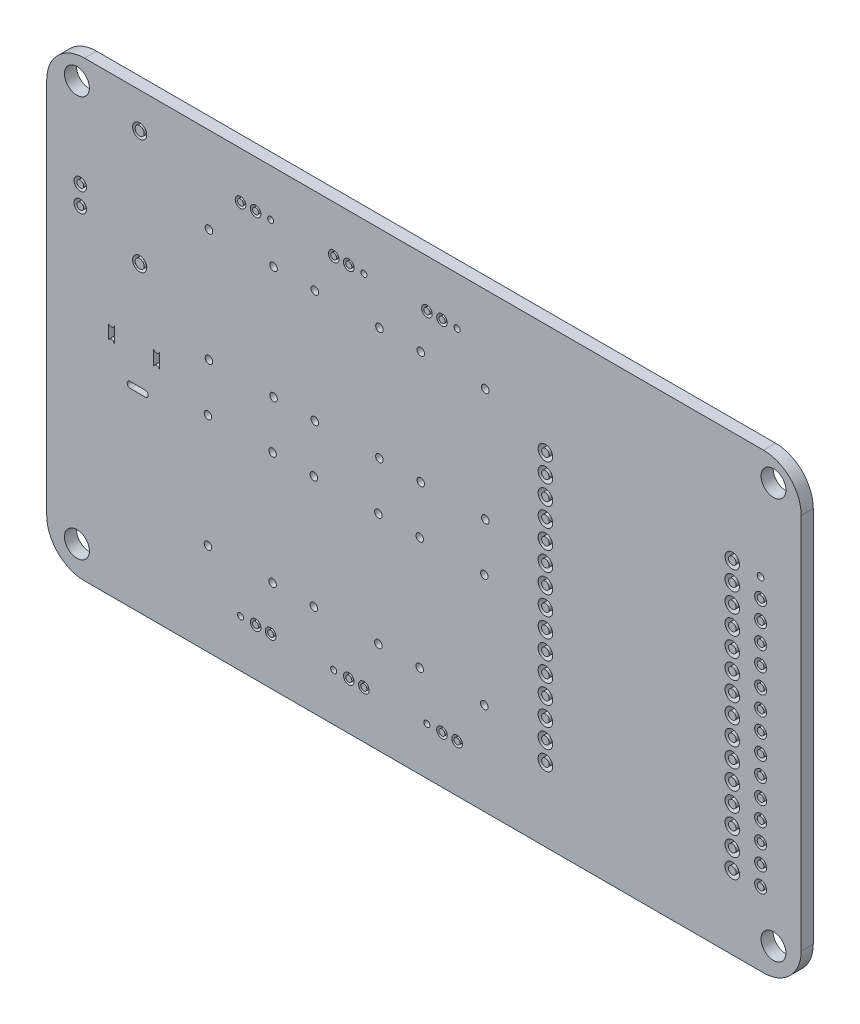
SolidWorks part; units mm, degrees
ref_plane "Front Plane" through (0, 0, 0) normal (0, 0, 1) x (1, 0, 0)
ref_plane "Top Plane" through (0, 0, 0) normal (0, 1, 0) x (1, 0, 0)
ref_plane "Right Plane" through (0, 0, 0) normal (1, 0, 0) x (0, 0, -1)
sketch "BoardOutLine" plane through (0, 0, 0) normal (0, 0, 1) x (1, 0, 0)
  line L0 (0, -55) -> (0, -5)
  line L1 (100, -5) -> (100, -55)
  line L2 (95, -60) -> (5, -60)
  line L3 (5, 0) -> (95, 0)
  line L4 (5, -5) -> (95, -55) construction
  line L6 (95, -5) -> (5, -55) construction
  arc A0 (100, -5) -> (95, 0) centre (95, -5) ccw
  arc A1 (0, -55) -> (5, -60) centre (5, -55) ccw
  arc A2 (5, 0) -> (0, -5) centre (5, -5) ccw
  arc A3 (95, -60) -> (100, -55) centre (95, -55) ccw
  dimension "D1" = 5
  dimension "D2" = 90
  dimension "D3" = 50
  dimension "D4" = 5
  dimension "D5" = 5
extrude "Boss-Extrude2" add sketch "BoardOutLine" along normal blind 1.6
sketch "Multi-Layer" plane through (0, 0, 1.6) normal (0, 0, 1) x (1, 0, 0)
  line L0 (90.3641, -50.3081) -> (90.3641, -50.3084)
  line L2 (91.3639, -50.3081) -> (91.3639, -50.3084)
  line L4 (90.3641, -47.7681) -> (90.3641, -47.7684)
  line L6 (91.3639, -47.7681) -> (91.3639, -47.7684)
  line L8 (90.3641, -45.2281) -> (90.3641, -45.2283)
  line L10 (91.3639, -45.2281) -> (91.3639, -45.2283)
  line L12 (90.3641, -42.6881) -> (90.3641, -42.6883)
  line L14 (91.3639, -42.6881) -> (91.3639, -42.6883)
  line L16 (90.3641, -40.1481) -> (90.3641, -40.1483)
  line L18 (91.3639, -40.1481) -> (91.3639, -40.1483)
  line L20 (90.3641, -37.6081) -> (90.3641, -37.6083)
  line L22 (91.3639, -37.6081) -> (91.3639, -37.6083)
  line L24 (90.3641, -35.0681) -> (90.3641, -35.0683)
  line L26 (91.3639, -35.0681) -> (91.3639, -35.0683)
  line L28 (90.3641, -32.5281) -> (90.3641, -32.5283)
  line L30 (91.3639, -32.5281) -> (91.3639, -32.5283)
  line L32 (90.3641, -29.9881) -> (90.3641, -29.9883)
  line L34 (91.3639, -29.9881) -> (91.3639, -29.9883)
  line L36 (90.3641, -27.4481) -> (90.3641, -27.4483)
  line L38 (91.3639, -27.4481) -> (91.3639, -27.4483)
  line L40 (90.3641, -24.9081) -> (90.3641, -24.9083)
  line L42 (91.3639, -24.9081) -> (91.3639, -24.9083)
  line L44 (90.3641, -22.368) -> (90.3641, -22.3683)
  line L46 (91.3639, -22.368) -> (91.3639, -22.3683)
  line L48 (90.3641, -19.828) -> (90.3641, -19.8283)
  line L50 (91.3639, -19.828) -> (91.3639, -19.8283)
  line L52 (90.3641, -17.288) -> (90.3641, -17.2883)
  line L54 (91.3639, -17.288) -> (91.3639, -17.2883)
  line L56 (90.3641, -14.748) -> (90.3641, -14.7483)
  line L58 (91.3639, -14.748) -> (91.3639, -14.7483)
  line L60 (65.594, -14.748) -> (65.594, -14.7483)
  line L62 (66.5937, -14.748) -> (66.5937, -14.7483)
  line L64 (65.594, -17.288) -> (65.594, -17.2883)
  line L66 (66.5937, -17.288) -> (66.5937, -17.2883)
  line L68 (65.594, -19.828) -> (65.594, -19.8283)
  line L70 (66.5937, -19.828) -> (66.5937, -19.8283)
  line L72 (65.594, -22.368) -> (65.594, -22.3683)
  line L74 (66.5937, -22.368) -> (66.5937, -22.3683)
  line L76 (65.594, -24.9081) -> (65.594, -24.9083)
  line L78 (66.5937, -24.9081) -> (66.5937, -24.9083)
  line L80 (65.594, -27.4481) -> (65.594, -27.4483)
  line L82 (66.5937, -27.4481) -> (66.5937, -27.4483)
  line L84 (65.594, -29.9881) -> (65.594, -29.9883)
  line L86 (66.5937, -29.9881) -> (66.5937, -29.9883)
  line L88 (65.594, -32.5281) -> (65.594, -32.5283)
  line L90 (66.5937, -32.5281) -> (66.5937, -32.5283)
  line L92 (65.594, -35.0681) -> (65.594, -35.0683)
  line L94 (66.5937, -35.0681) -> (66.5937, -35.0683)
  line L96 (65.594, -37.6081) -> (65.594, -37.6083)
  line L98 (66.5937, -37.6081) -> (66.5937, -37.6083)
  line L100 (65.594, -40.1481) -> (65.594, -40.1483)
  line L102 (66.5937, -40.1481) -> (66.5937, -40.1483)
  line L104 (65.594, -42.6881) -> (65.594, -42.6883)
  line L106 (66.5937, -42.6881) -> (66.5937, -42.6883)
  line L108 (65.594, -45.2281) -> (65.594, -45.2283)
  line L110 (66.5937, -45.2281) -> (66.5937, -45.2283)
  line L112 (65.594, -47.7681) -> (65.594, -47.7684)
  line L114 (66.5937, -47.7681) -> (66.5937, -47.7684)
  line L116 (65.594, -50.3081) -> (65.594, -50.3084)
  line L118 (66.5937, -50.3081) -> (66.5937, -50.3084)
  line L120 (13.0572, -34.0812) -> (11.0572, -34.0812)
  line L122 (13.0572, -34.8812) -> (11.0572, -34.8812)
  line L124 (8.1571, -30.8809) -> (8.1571, -28.6809)
  line L126 (8.9571, -30.8809) -> (8.9571, -28.6809)
  line L128 (14.1568, -28.6811) -> (14.1568, -30.8811)
  line L130 (14.9568, -28.6811) -> (14.9568, -30.8811)
  circle A0 centre (12.319, -4.699) radius 0.5994
  circle A1 centre (12.319, -4.699) radius 0.9398
  circle A2 centre (12.319, -19.939) radius 0.5994
  circle A3 centre (12.319, -19.939) radius 0.9398
  circle A4 centre (4.445, -14.732) radius 0.45
  circle A5 centre (4.445, -14.732) radius 0.8255
  circle A6 centre (4.445, -17.272) radius 0.45
  circle A7 centre (4.445, -17.272) radius 0.8255
  arc A8 (90.3641, -50.3084) -> (91.3639, -50.3084) centre (90.864, -50.3084) ccw
  arc A9 (91.3639, -50.3081) -> (90.3641, -50.3081) centre (90.864, -50.3081) ccw
  circle A10 centre (90.8641, -50.3084) radius 0.9652
  arc A11 (90.3641, -47.7684) -> (91.3639, -47.7684) centre (90.864, -47.7684) ccw
  arc A12 (91.3639, -47.7681) -> (90.3641, -47.7681) centre (90.864, -47.7681) ccw
  circle A13 centre (90.8641, -47.7684) radius 0.9652
  arc A14 (90.3641, -45.2283) -> (91.3639, -45.2283) centre (90.864, -45.2283) ccw
  arc A15 (91.3639, -45.2281) -> (90.3641, -45.2281) centre (90.864, -45.2281) ccw
  circle A16 centre (90.8641, -45.2283) radius 0.9652
  arc A17 (90.3641, -42.6883) -> (91.3639, -42.6883) centre (90.864, -42.6883) ccw
  arc A18 (91.3639, -42.6881) -> (90.3641, -42.6881) centre (90.864, -42.6881) ccw
  circle A19 centre (90.8641, -42.6883) radius 0.9652
  arc A20 (90.3641, -40.1483) -> (91.3639, -40.1483) centre (90.864, -40.1483) ccw
  arc A21 (91.3639, -40.1481) -> (90.3641, -40.1481) centre (90.864, -40.1481) ccw
  circle A22 centre (90.8641, -40.1483) radius 0.9652
  arc A23 (90.3641, -37.6083) -> (91.3639, -37.6083) centre (90.864, -37.6083) ccw
  arc A24 (91.3639, -37.6081) -> (90.3641, -37.6081) centre (90.864, -37.6081) ccw
  circle A25 centre (90.8641, -37.6083) radius 0.9652
  arc A26 (90.3641, -35.0683) -> (91.3639, -35.0683) centre (90.864, -35.0683) ccw
  arc A27 (91.3639, -35.0681) -> (90.3641, -35.0681) centre (90.864, -35.0681) ccw
  circle A28 centre (90.8641, -35.0683) radius 0.9652
  arc A29 (90.3641, -32.5283) -> (91.3639, -32.5283) centre (90.864, -32.5283) ccw
  arc A30 (91.3639, -32.5281) -> (90.3641, -32.5281) centre (90.864, -32.5281) ccw
  circle A31 centre (90.8641, -32.5283) radius 0.9652
  arc A32 (90.3641, -29.9883) -> (91.3639, -29.9883) centre (90.864, -29.9883) ccw
  arc A33 (91.3639, -29.9881) -> (90.3641, -29.9881) centre (90.864, -29.9881) ccw
  circle A34 centre (90.8641, -29.9883) radius 0.9652
  arc A35 (90.3641, -27.4483) -> (91.3639, -27.4483) centre (90.864, -27.4483) ccw
  arc A36 (91.3639, -27.4481) -> (90.3641, -27.4481) centre (90.864, -27.4481) ccw
  circle A37 centre (90.8641, -27.4483) radius 0.9652
  arc A38 (90.3641, -24.9083) -> (91.3639, -24.9083) centre (90.864, -24.9083) ccw
  arc A39 (91.3639, -24.9081) -> (90.3641, -24.9081) centre (90.864, -24.9081) ccw
  circle A40 centre (90.8641, -24.9083) radius 0.9652
  arc A41 (90.3641, -22.3683) -> (91.3639, -22.3683) centre (90.864, -22.3683) ccw
  arc A42 (91.3639, -22.368) -> (90.3641, -22.368) centre (90.864, -22.368) ccw
  circle A43 centre (90.8641, -22.3683) radius 0.9652
  arc A44 (90.3641, -19.8283) -> (91.3639, -19.8283) centre (90.864, -19.8283) ccw
  arc A45 (91.3639, -19.828) -> (90.3641, -19.828) centre (90.864, -19.828) ccw
  circle A46 centre (90.8641, -19.8283) radius 0.9652
  arc A47 (90.3641, -17.2883) -> (91.3639, -17.2883) centre (90.864, -17.2883) ccw
  arc A48 (91.3639, -17.288) -> (90.3641, -17.288) centre (90.864, -17.288) ccw
  circle A49 centre (90.8641, -17.2883) radius 0.9652
  arc A50 (90.3641, -14.7483) -> (91.3639, -14.7483) centre (90.864, -14.7483) ccw
  arc A51 (91.3639, -14.748) -> (90.3641, -14.748) centre (90.864, -14.748) ccw
  circle A52 centre (90.8641, -14.7483) radius 0.9652
  arc A53 (65.594, -14.7483) -> (66.5937, -14.7483) centre (66.0939, -14.7483) ccw
  arc A54 (66.5937, -14.748) -> (65.594, -14.748) centre (66.0939, -14.748) ccw
  circle A55 centre (66.094, -14.7483) radius 0.9652
  arc A56 (65.594, -17.2883) -> (66.5937, -17.2883) centre (66.0939, -17.2883) ccw
  arc A57 (66.5937, -17.288) -> (65.594, -17.288) centre (66.0939, -17.288) ccw
  circle A58 centre (66.094, -17.2883) radius 0.9652
  arc A59 (65.594, -19.8283) -> (66.5937, -19.8283) centre (66.0939, -19.8283) ccw
  arc A60 (66.5937, -19.828) -> (65.594, -19.828) centre (66.0939, -19.828) ccw
  circle A61 centre (66.094, -19.8283) radius 0.9652
  arc A62 (65.594, -22.3683) -> (66.5937, -22.3683) centre (66.0939, -22.3683) ccw
  arc A63 (66.5937, -22.368) -> (65.594, -22.368) centre (66.0939, -22.368) ccw
  circle A64 centre (66.094, -22.3683) radius 0.9652
  arc A65 (65.594, -24.9083) -> (66.5937, -24.9083) centre (66.0939, -24.9083) ccw
  arc A66 (66.5937, -24.9081) -> (65.594, -24.9081) centre (66.0939, -24.9081) ccw
  circle A67 centre (66.094, -24.9083) radius 0.9652
  arc A68 (65.594, -27.4483) -> (66.5937, -27.4483) centre (66.0939, -27.4483) ccw
  arc A69 (66.5937, -27.4481) -> (65.594, -27.4481) centre (66.0939, -27.4481) ccw
  circle A70 centre (66.094, -27.4483) radius 0.9652
  arc A71 (65.594, -29.9883) -> (66.5937, -29.9883) centre (66.0939, -29.9883) ccw
  arc A72 (66.5937, -29.9881) -> (65.594, -29.9881) centre (66.0939, -29.9881) ccw
  circle A73 centre (66.094, -29.9883) radius 0.9652
  arc A74 (65.594, -32.5283) -> (66.5937, -32.5283) centre (66.0939, -32.5283) ccw
  arc A75 (66.5937, -32.5281) -> (65.594, -32.5281) centre (66.0939, -32.5281) ccw
  circle A76 centre (66.094, -32.5283) radius 0.9652
  arc A77 (65.594, -35.0683) -> (66.5937, -35.0683) centre (66.0939, -35.0683) ccw
  arc A78 (66.5937, -35.0681) -> (65.594, -35.0681) centre (66.0939, -35.0681) ccw
  circle A79 centre (66.094, -35.0683) radius 0.9652
  arc A80 (65.594, -37.6083) -> (66.5937, -37.6083) centre (66.0939, -37.6083) ccw
  arc A81 (66.5937, -37.6081) -> (65.594, -37.6081) centre (66.0939, -37.6081) ccw
  circle A82 centre (66.094, -37.6083) radius 0.9652
  arc A83 (65.594, -40.1483) -> (66.5937, -40.1483) centre (66.0939, -40.1483) ccw
  arc A84 (66.5937, -40.1481) -> (65.594, -40.1481) centre (66.0939, -40.1481) ccw
  circle A85 centre (66.094, -40.1483) radius 0.9652
  arc A86 (65.594, -42.6883) -> (66.5937, -42.6883) centre (66.0939, -42.6883) ccw
  arc A87 (66.5937, -42.6881) -> (65.594, -42.6881) centre (66.0939, -42.6881) ccw
  circle A88 centre (66.094, -42.6883) radius 0.9652
  arc A89 (65.594, -45.2283) -> (66.5937, -45.2283) centre (66.0939, -45.2283) ccw
  arc A90 (66.5937, -45.2281) -> (65.594, -45.2281) centre (66.0939, -45.2281) ccw
  circle A91 centre (66.094, -45.2283) radius 0.9652
  arc A92 (65.594, -47.7684) -> (66.5937, -47.7684) centre (66.0939, -47.7684) ccw
  arc A93 (66.5937, -47.7681) -> (65.594, -47.7681) centre (66.0939, -47.7681) ccw
  circle A94 centre (66.094, -47.7684) radius 0.9652
  arc A95 (65.594, -50.3084) -> (66.5937, -50.3084) centre (66.0939, -50.3084) ccw
  arc A96 (66.5937, -50.3081) -> (65.594, -50.3081) centre (66.0939, -50.3081) ccw
  circle A97 centre (66.094, -50.3084) radius 0.9652
  circle A98 centre (94.6152, -50.2921) radius 0.4445
  circle A99 centre (94.6152, -50.2921) radius 0.7874
  circle A100 centre (94.6152, -47.7521) radius 0.4445
  circle A101 centre (94.6152, -47.7521) radius 0.7874
  circle A102 centre (94.6152, -45.2121) radius 0.4445
  circle A103 centre (94.6152, -45.2121) radius 0.7874
  circle A104 centre (94.6152, -42.6721) radius 0.4445
  circle A105 centre (94.6152, -42.6721) radius 0.7874
  circle A106 centre (94.6152, -40.1321) radius 0.4445
  circle A107 centre (94.6152, -40.1321) radius 0.7874
  circle A108 centre (94.6152, -37.5921) radius 0.4445
  circle A109 centre (94.6152, -37.5921) radius 0.7874
  circle A110 centre (94.6152, -35.0521) radius 0.4445
  circle A111 centre (94.6152, -35.0521) radius 0.7874
  circle A112 centre (94.6152, -32.5121) radius 0.4445
  circle A113 centre (94.6152, -32.5121) radius 0.7874
  circle A114 centre (94.6152, -29.9721) radius 0.4445
  circle A115 centre (94.6152, -29.9721) radius 0.7874
  circle A116 centre (94.6152, -27.4321) radius 0.4445
  circle A117 centre (94.6152, -27.4321) radius 0.7874
  circle A118 centre (94.6152, -24.892) radius 0.4445
  circle A119 centre (94.6152, -24.892) radius 0.7874
  circle A120 centre (94.6152, -22.352) radius 0.4445
  circle A121 centre (94.6152, -22.352) radius 0.7874
  circle A122 centre (94.6152, -19.812) radius 0.4445
  circle A123 centre (94.6152, -19.812) radius 0.7874
  circle A124 centre (94.6152, -17.272) radius 0.4445
  circle A125 centre (94.6152, -17.272) radius 0.7874
  circle A126 centre (40.0368, -6.223) radius 0.4
  circle A127 centre (40.0368, -6.223) radius 0.7
  circle A128 centre (38.0368, -6.223) radius 0.4
  circle A129 centre (38.0368, -6.223) radius 0.7
  circle A130 centre (52.3876, -6.35) radius 0.4
  circle A131 centre (52.3876, -6.35) radius 0.7
  circle A132 centre (50.3876, -6.35) radius 0.4
  circle A133 centre (50.3876, -6.35) radius 0.7
  circle A134 centre (40.0368, -53.7211) radius 0.4
  circle A135 centre (40.0368, -53.7211) radius 0.7
  circle A136 centre (42.0368, -53.7211) radius 0.4
  circle A137 centre (42.0368, -53.7211) radius 0.7
  circle A138 centre (52.3876, -53.7211) radius 0.4
  circle A139 centre (52.3876, -53.7211) radius 0.7
  circle A140 centre (54.3876, -53.7211) radius 0.4
  circle A141 centre (54.3876, -53.7211) radius 0.7
  circle A142 centre (27.6861, -6.223) radius 0.4
  circle A143 centre (27.6861, -6.223) radius 0.7
  circle A144 centre (25.6861, -6.223) radius 0.4
  circle A145 centre (25.6861, -6.223) radius 0.7
  circle A146 centre (27.6861, -53.7211) radius 0.4
  circle A147 centre (27.6861, -53.7211) radius 0.7
  circle A148 centre (29.6861, -53.7211) radius 0.4
  circle A149 centre (29.6861, -53.7211) radius 0.7
  circle A150 centre (44.0961, -11.4149) radius 0.5
  circle A151 centre (35.5373, -11.4149) radius 0.5
  circle A152 centre (44.0961, -26.3802) radius 0.5
  circle A153 centre (35.5373, -26.3802) radius 0.5
  circle A154 centre (58.1296, -11.4149) radius 0.5
  circle A155 centre (49.5708, -11.4149) radius 0.5
  circle A156 centre (58.1296, -26.3802) radius 0.5
  circle A157 centre (49.5708, -26.3802) radius 0.5
  circle A158 centre (30.0626, -11.4149) radius 0.5
  circle A159 centre (21.5038, -11.4149) radius 0.5
  circle A160 centre (30.0626, -26.3802) radius 0.5
  circle A161 centre (21.5038, -26.3802) radius 0.5
  circle A162 centre (49.4396, -47.7672) radius 0.5
  circle A163 centre (57.9984, -47.7672) radius 0.5
  circle A164 centre (49.4396, -32.802) radius 0.5
  circle A165 centre (57.9984, -32.802) radius 0.5
  circle A166 centre (35.406, -47.7672) radius 0.5
  circle A167 centre (43.9648, -47.7672) radius 0.5
  circle A168 centre (35.406, -32.802) radius 0.5
  circle A169 centre (43.9648, -32.802) radius 0.5
  circle A170 centre (21.3725, -47.7672) radius 0.5
  circle A171 centre (29.9313, -47.7672) radius 0.5
  circle A172 centre (21.3725, -32.802) radius 0.5
  circle A173 centre (29.9313, -32.802) radius 0.5
  circle A174 centre (94.6152, -14.732) radius 0.4445
  arc A175 (11.0572, -34.0812) -> (11.0572, -34.8812) centre (11.0572, -34.4812) ccw
  arc A176 (13.0572, -34.8812) -> (13.0572, -34.0812) centre (13.0572, -34.4812) ccw
  arc A177 (8.9571, -30.8809) -> (8.1571, -30.8809) centre (8.5571, -30.8809) ccw
  arc A178 (8.1571, -28.6809) -> (8.9571, -28.6809) centre (8.5571, -28.6809) ccw
  arc A179 (14.1568, -28.6811) -> (14.9568, -28.6811) centre (14.5568, -28.6811) ccw
  arc A180 (14.9568, -30.8811) -> (14.1568, -30.8811) centre (14.5568, -30.8811) ccw
  circle A181 centre (42.0368, -6.223) radius 0.4
  circle A182 centre (54.3876, -6.35) radius 0.4
  circle A183 centre (38.0368, -53.7211) radius 0.4
  circle A184 centre (50.3876, -53.7211) radius 0.4
  circle A185 centre (29.6861, -6.223) radius 0.4
  circle A186 centre (25.6861, -53.7211) radius 0.4
  circle A187 centre (96.3297, -3.1115) radius 1.65
  circle A188 centre (4.0005, -3.1115) radius 1.65
  circle A189 centre (96.3297, -56.2611) radius 1.65
  circle A190 centre (4.0005, -56.2611) radius 1.65
extrude "Cut-Extrude2" cut sketch "Multi-Layer" against normal up to next (1.6 mm away)
sketch "BottomLayer" plane through (0, 0, 0) normal (0, 0, 1) x (1, 0, 0)
  line L0 (65.2082, -47.5949) -> (65.3816, -47.7684)
  line L2 (49.5708, -11.4148) -> (52.4663, -11.4148)
  line L3 (52.4663, -11.4148) -> (54.3876, -9.4935)
  line L4 (54.3876, -9.4935) -> (54.3876, -6.35)
  line L5 (29.9313, -32.8019) -> (30.5944, -34.4044)
  line L6 (30.5944, -34.4044) -> (32.8931, -36.7031)
  line L7 (32.8931, -36.7031) -> (42.2911, -36.7031)
  line L8 (42.2911, -36.7031) -> (43.3071, -35.6871)
  line L9 (43.3071, -35.6871) -> (43.9648, -32.8019)
  line L10 (43.9648, -32.8019) -> (44.0691, -35.6871)
  line L11 (44.0691, -35.6871) -> (44.9581, -36.7031)
  line L12 (44.9581, -36.7031) -> (56.1341, -36.7031)
  line L13 (56.1341, -36.7031) -> (58.0391, -34.5441)
  line L14 (58.0391, -34.5441) -> (57.9984, -32.8019)
  line L15 (29.9313, -47.7673) -> (27.1628, -47.7673)
  line L16 (27.1628, -47.7673) -> (25.6871, -49.2431)
  line L17 (25.6871, -49.2431) -> (25.6871, -53.7211)
  line L18 (57.9984, -47.7673) -> (53.5789, -47.7673)
  line L19 (53.5789, -47.7673) -> (50.3886, -50.9576)
  line L20 (50.3886, -50.9576) -> (50.3886, -53.7211)
  line L21 (49.5708, -26.3802) -> (49.5708, -11.4148)
  line L22 (57.9984, -47.7673) -> (57.9984, -32.8019)
  line L23 (43.9648, -32.8019) -> (43.9648, -47.7673)
  line L24 (29.9313, -47.7673) -> (29.9313, -32.8019)
  line L25 (35.5373, -26.3802) -> (38.3312, -23.114)
  line L26 (38.3312, -23.114) -> (46.0224, -23.114)
  line L27 (46.0224, -23.114) -> (49.5708, -26.3802)
  line L28 (21.5038, -26.3802) -> (24.8692, -22.352)
  line L29 (24.8692, -22.352) -> (31.0363, -22.352)
  line L30 (31.0363, -22.352) -> (35.5373, -26.3802)
  line L31 (35.5373, -26.3802) -> (35.5373, -11.4148)
  line L32 (21.5038, -26.3802) -> (21.5038, -11.4148)
  line L33 (57.9984, -47.7673) -> (57.9994, -47.7684)
  line L34 (57.9994, -47.7684) -> (66.094, -47.7684)
  line L35 (52.3876, -53.7211) -> (52.3876, -52.1336)
  line L36 (52.3876, -52.1336) -> (54.2129, -50.3084)
  line L37 (54.2129, -50.3084) -> (66.094, -50.3084)
  line L38 (21.5038, -26.3802) -> (16.5456, -26.3805)
  line L39 (16.5456, -26.3805) -> (14.5568, -28.3693)
  line L40 (14.5568, -28.3693) -> (14.5568, -29.7816)
  line L41 (14.5568, -29.7816) -> (14.5568, -31.4478)
  line L42 (14.5568, -31.4478) -> (19.304, -36.1951)
  line L43 (19.304, -36.1951) -> (28.0467, -36.1951)
  line L44 (28.0467, -36.1951) -> (29.9416, -34.3002)
  line L45 (29.9416, -34.3002) -> (29.9313, -32.8019)
  line L46 (14.5568, -29.7816) -> (4.445, -19.6694)
  line L47 (4.445, -19.6694) -> (4.445, -17.272)
  line L48 (21.5038, -11.4148) -> (26.0503, -11.4148)
  line L49 (26.0503, -11.4148) -> (29.685, -7.78)
  line L50 (29.685, -7.78) -> (29.685, -6.223)
  line L51 (43.9648, -47.7673) -> (40.2438, -47.7673)
  line L52 (40.2438, -47.7673) -> (38.1001, -50.2921)
  line L53 (38.1001, -50.2921) -> (38.0368, -53.7211)
  line L54 (35.5373, -11.4148) -> (39.2583, -11.4148)
  line L55 (39.2583, -11.4148) -> (42.0371, -8.636)
  line L56 (42.0371, -8.636) -> (42.0371, -6.223)
sketch "BottomSilkLayer" plane through (0, 0, 0) normal (0, 0, 1) x (1, 0, 0)
  line L0 (82.4232, -18.034) -> (82.4232, -44.5136) construction
  line L1 (78.6132, -22.225) -> (78.6132, -40.5131) construction
  text T0 "Manipulator Board V1" font "ARIAL" height 2.032
  text T1 "Tamir Mhabary" font "ARIAL" height 2.032
sketch "BottomSolderMaskLayer" plane through (0, 0, 0) normal (0, 0, 1) x (1, 0, 0)
  line L0 (90.351, -50.3081) -> (90.351, -50.3084)
  line L1 (90.351, -50.3084) -> (90.351, -50.3081)
  line L2 (91.377, -50.3081) -> (91.377, -50.3084)
  line L3 (91.377, -50.3084) -> (91.377, -50.3081)
  line L4 (90.351, -47.7681) -> (90.351, -47.7684)
  line L5 (90.351, -47.7684) -> (90.351, -47.7681)
  line L6 (91.377, -47.7681) -> (91.377, -47.7684)
  line L7 (91.377, -47.7684) -> (91.377, -47.7681)
  line L8 (90.351, -45.2281) -> (90.351, -45.2283)
  line L9 (90.351, -45.2283) -> (90.351, -45.2281)
  line L10 (91.377, -45.2281) -> (91.377, -45.2283)
  line L11 (91.377, -45.2283) -> (91.377, -45.2281)
  line L12 (90.351, -42.6881) -> (90.351, -42.6883)
  line L13 (90.351, -42.6883) -> (90.351, -42.6881)
  line L14 (91.377, -42.6881) -> (91.377, -42.6883)
  line L15 (91.377, -42.6883) -> (91.377, -42.6881)
  line L16 (90.351, -40.1481) -> (90.351, -40.1483)
  line L17 (90.351, -40.1483) -> (90.351, -40.1481)
  line L18 (91.377, -40.1481) -> (91.377, -40.1483)
  line L19 (91.377, -40.1483) -> (91.377, -40.1481)
  line L20 (90.351, -37.6081) -> (90.351, -37.6083)
  line L21 (90.351, -37.6083) -> (90.351, -37.6081)
  line L22 (91.377, -37.6081) -> (91.377, -37.6083)
  line L23 (91.377, -37.6083) -> (91.377, -37.6081)
  line L24 (90.351, -35.0681) -> (90.351, -35.0683)
  line L25 (90.351, -35.0683) -> (90.351, -35.0681)
  line L26 (91.377, -35.0681) -> (91.377, -35.0683)
  line L27 (91.377, -35.0683) -> (91.377, -35.0681)
  line L28 (90.351, -32.5281) -> (90.351, -32.5283)
  line L29 (90.351, -32.5283) -> (90.351, -32.5281)
  line L30 (91.377, -32.5281) -> (91.377, -32.5283)
  line L31 (91.377, -32.5283) -> (91.377, -32.5281)
  line L32 (90.351, -29.9881) -> (90.351, -29.9883)
  line L33 (90.351, -29.9883) -> (90.351, -29.9881)
  line L34 (91.377, -29.9881) -> (91.377, -29.9883)
  line L35 (91.377, -29.9883) -> (91.377, -29.9881)
  line L36 (90.351, -27.4481) -> (90.351, -27.4483)
  line L37 (90.351, -27.4483) -> (90.351, -27.4481)
  line L38 (91.377, -27.4481) -> (91.377, -27.4483)
  line L39 (91.377, -27.4483) -> (91.377, -27.4481)
  line L40 (90.351, -24.908) -> (90.351, -24.9083)
  line L41 (90.351, -24.9083) -> (90.351, -24.908)
  line L42 (91.377, -24.908) -> (91.377, -24.9083)
  line L43 (91.377, -24.9083) -> (91.377, -24.908)
  line L44 (90.351, -22.368) -> (90.351, -22.3683)
  line L45 (90.351, -22.3683) -> (90.351, -22.368)
  line L46 (91.377, -22.368) -> (91.377, -22.3683)
  line L47 (91.377, -22.3683) -> (91.377, -22.368)
  line L48 (90.351, -19.828) -> (90.351, -19.8283)
  line L49 (90.351, -19.8283) -> (90.351, -19.828)
  line L50 (91.377, -19.828) -> (91.377, -19.8283)
  line L51 (91.377, -19.8283) -> (91.377, -19.828)
  line L52 (90.351, -17.288) -> (90.351, -17.2883)
  line L53 (90.351, -17.2883) -> (90.351, -17.288)
  line L54 (91.377, -17.288) -> (91.377, -17.2883)
  line L55 (91.377, -17.2883) -> (91.377, -17.288)
  line L56 (90.351, -14.748) -> (90.351, -14.7483)
  line L57 (90.351, -14.7483) -> (90.351, -14.748)
  line L58 (91.377, -14.748) -> (91.377, -14.7483)
  line L59 (91.377, -14.7483) -> (91.377, -14.748)
  line L60 (65.5808, -14.748) -> (65.5808, -14.7483)
  line L61 (65.5808, -14.7483) -> (65.5808, -14.748)
  line L62 (66.6069, -14.748) -> (66.6069, -14.7483)
  line L63 (66.6069, -14.7483) -> (66.6069, -14.748)
  line L64 (65.5808, -17.288) -> (65.5808, -17.2883)
  line L65 (65.5808, -17.2883) -> (65.5808, -17.288)
  line L66 (66.6069, -17.288) -> (66.6069, -17.2883)
  line L67 (66.6069, -17.2883) -> (66.6069, -17.288)
  line L68 (65.5808, -19.828) -> (65.5808, -19.8283)
  line L69 (65.5808, -19.8283) -> (65.5808, -19.828)
  line L70 (66.6069, -19.828) -> (66.6069, -19.8283)
  line L71 (66.6069, -19.8283) -> (66.6069, -19.828)
  line L72 (65.5808, -22.368) -> (65.5808, -22.3683)
  line L73 (65.5808, -22.3683) -> (65.5808, -22.368)
  line L74 (66.6069, -22.368) -> (66.6069, -22.3683)
  line L75 (66.6069, -22.3683) -> (66.6069, -22.368)
  line L76 (65.5808, -24.908) -> (65.5808, -24.9083)
  line L77 (65.5808, -24.9083) -> (65.5808, -24.908)
  line L78 (66.6069, -24.908) -> (66.6069, -24.9083)
  line L79 (66.6069, -24.9083) -> (66.6069, -24.908)
  line L80 (65.5808, -27.4481) -> (65.5808, -27.4483)
  line L81 (65.5808, -27.4483) -> (65.5808, -27.4481)
  line L82 (66.6069, -27.4481) -> (66.6069, -27.4483)
  line L83 (66.6069, -27.4483) -> (66.6069, -27.4481)
  line L84 (65.5808, -29.9881) -> (65.5808, -29.9883)
  line L85 (65.5808, -29.9883) -> (65.5808, -29.9881)
  line L86 (66.6069, -29.9881) -> (66.6069, -29.9883)
  line L87 (66.6069, -29.9883) -> (66.6069, -29.9881)
  line L88 (65.5808, -32.5281) -> (65.5808, -32.5283)
  line L89 (65.5808, -32.5283) -> (65.5808, -32.5281)
  line L90 (66.6069, -32.5281) -> (66.6069, -32.5283)
  line L91 (66.6069, -32.5283) -> (66.6069, -32.5281)
  line L92 (65.5808, -35.0681) -> (65.5808, -35.0683)
  line L93 (65.5808, -35.0683) -> (65.5808, -35.0681)
  line L94 (66.6069, -35.0681) -> (66.6069, -35.0683)
  line L95 (66.6069, -35.0683) -> (66.6069, -35.0681)
  line L96 (65.5808, -37.6081) -> (65.5808, -37.6083)
  line L97 (65.5808, -37.6083) -> (65.5808, -37.6081)
  line L98 (66.6069, -37.6081) -> (66.6069, -37.6083)
  line L99 (66.6069, -37.6083) -> (66.6069, -37.6081)
  line L100 (65.5808, -40.1481) -> (65.5808, -40.1483)
  line L101 (65.5808, -40.1483) -> (65.5808, -40.1481)
  line L102 (66.6069, -40.1481) -> (66.6069, -40.1483)
  line L103 (66.6069, -40.1483) -> (66.6069, -40.1481)
  line L104 (65.5808, -42.6881) -> (65.5808, -42.6883)
  line L105 (65.5808, -42.6883) -> (65.5808, -42.6881)
  line L106 (66.6069, -42.6881) -> (66.6069, -42.6883)
  line L107 (66.6069, -42.6883) -> (66.6069, -42.6881)
  line L108 (65.5808, -45.2281) -> (65.5808, -45.2283)
  line L109 (65.5808, -45.2283) -> (65.5808, -45.2281)
  line L110 (66.6069, -45.2281) -> (66.6069, -45.2283)
  line L111 (66.6069, -45.2283) -> (66.6069, -45.2281)
  line L112 (65.5808, -47.7681) -> (65.5808, -47.7684)
  line L113 (65.5808, -47.7684) -> (65.5808, -47.7681)
  line L114 (66.6069, -47.7681) -> (66.6069, -47.7684)
  line L115 (66.6069, -47.7684) -> (66.6069, -47.7681)
  line L116 (65.5808, -50.3081) -> (65.5808, -50.3084)
  line L117 (65.5808, -50.3084) -> (65.5808, -50.3081)
  line L118 (66.6069, -50.3081) -> (66.6069, -50.3084)
  line L119 (66.6069, -50.3084) -> (66.6069, -50.3081)
  line L120 (13.0713, -34.0756) -> (11.0431, -34.0756)
  line L121 (11.0431, -34.0756) -> (13.0713, -34.0756)
  line L122 (13.0713, -34.8868) -> (11.0431, -34.8868)
  line L123 (11.0431, -34.8868) -> (13.0713, -34.8868)
  line L124 (8.1444, -30.8956) -> (8.1444, -28.6662)
  line L125 (8.1444, -28.6662) -> (8.1444, -30.8956)
  line L126 (8.9698, -30.8956) -> (8.9698, -28.6662)
  line L127 (8.9698, -28.6662) -> (8.9698, -30.8956)
  line L128 (14.1441, -28.6663) -> (14.1441, -30.8958)
  line L129 (14.1441, -30.8958) -> (14.1441, -28.6663)
  line L130 (14.9695, -28.6663) -> (14.9695, -30.8958)
  line L131 (14.9695, -30.8958) -> (14.9695, -28.6663)
  circle A0 centre (12.319, -4.699) radius 0.6156
  circle A1 centre (12.319, -4.699) radius 0.9652
  circle A2 centre (12.319, -19.939) radius 0.6156
  circle A3 centre (12.319, -19.939) radius 0.9652
  circle A4 centre (4.445, -14.732) radius 0.4639
  circle A5 centre (4.445, -14.732) radius 0.8509
  circle A6 centre (4.445, -17.272) radius 0.4639
  circle A7 centre (4.445, -17.272) radius 0.8509
  arc A8 (90.351, -50.3084) -> (91.377, -50.3084) centre (90.864, -50.3084) ccw
  arc A9 (91.377, -50.3081) -> (90.351, -50.3081) centre (90.864, -50.3081) ccw
  circle A10 centre (90.8641, -50.3084) radius 0.9906
  arc A11 (90.351, -47.7684) -> (91.377, -47.7684) centre (90.864, -47.7684) ccw
  arc A12 (91.377, -47.7681) -> (90.351, -47.7681) centre (90.864, -47.7681) ccw
  circle A13 centre (90.8641, -47.7684) radius 0.9906
  arc A14 (90.351, -45.2283) -> (91.377, -45.2283) centre (90.864, -45.2283) ccw
  arc A15 (91.377, -45.2281) -> (90.351, -45.2281) centre (90.864, -45.2281) ccw
  circle A16 centre (90.8641, -45.2283) radius 0.9906
  arc A17 (90.351, -42.6883) -> (91.377, -42.6883) centre (90.864, -42.6883) ccw
  arc A18 (91.377, -42.6881) -> (90.351, -42.6881) centre (90.864, -42.6881) ccw
  circle A19 centre (90.8641, -42.6883) radius 0.9906
  arc A20 (90.351, -40.1483) -> (91.377, -40.1483) centre (90.864, -40.1483) ccw
  arc A21 (91.377, -40.1481) -> (90.351, -40.1481) centre (90.864, -40.1481) ccw
  circle A22 centre (90.8641, -40.1483) radius 0.9906
  arc A23 (90.351, -37.6083) -> (91.377, -37.6083) centre (90.864, -37.6083) ccw
  arc A24 (91.377, -37.6081) -> (90.351, -37.6081) centre (90.864, -37.6081) ccw
  circle A25 centre (90.8641, -37.6083) radius 0.9906
  arc A26 (90.351, -35.0683) -> (91.377, -35.0683) centre (90.864, -35.0683) ccw
  arc A27 (91.377, -35.0681) -> (90.351, -35.0681) centre (90.864, -35.0681) ccw
  circle A28 centre (90.8641, -35.0683) radius 0.9906
  arc A29 (90.351, -32.5283) -> (91.377, -32.5283) centre (90.864, -32.5283) ccw
  arc A30 (91.377, -32.5281) -> (90.351, -32.5281) centre (90.864, -32.5281) ccw
  circle A31 centre (90.8641, -32.5283) radius 0.9906
  arc A32 (90.351, -29.9883) -> (91.377, -29.9883) centre (90.864, -29.9883) ccw
  arc A33 (91.377, -29.9881) -> (90.351, -29.9881) centre (90.864, -29.9881) ccw
  circle A34 centre (90.8641, -29.9883) radius 0.9906
  arc A35 (90.351, -27.4483) -> (91.377, -27.4483) centre (90.864, -27.4483) ccw
  arc A36 (91.377, -27.4481) -> (90.351, -27.4481) centre (90.864, -27.4481) ccw
  circle A37 centre (90.8641, -27.4483) radius 0.9906
  arc A38 (90.351, -24.9083) -> (91.377, -24.9083) centre (90.864, -24.9083) ccw
  arc A39 (91.377, -24.908) -> (90.351, -24.908) centre (90.864, -24.908) ccw
  circle A40 centre (90.8641, -24.9083) radius 0.9906
  arc A41 (90.351, -22.3683) -> (91.377, -22.3683) centre (90.864, -22.3683) ccw
  arc A42 (91.377, -22.368) -> (90.351, -22.368) centre (90.864, -22.368) ccw
  circle A43 centre (90.8641, -22.3683) radius 0.9906
  arc A44 (90.351, -19.8283) -> (91.377, -19.8283) centre (90.864, -19.8283) ccw
  arc A45 (91.377, -19.828) -> (90.351, -19.828) centre (90.864, -19.828) ccw
  circle A46 centre (90.8641, -19.8283) radius 0.9906
  arc A47 (90.351, -17.2883) -> (91.377, -17.2883) centre (90.864, -17.2883) ccw
  arc A48 (91.377, -17.288) -> (90.351, -17.288) centre (90.864, -17.288) ccw
  circle A49 centre (90.8641, -17.2883) radius 0.9906
  arc A50 (90.351, -14.7483) -> (91.377, -14.7483) centre (90.864, -14.7483) ccw
  arc A51 (91.377, -14.748) -> (90.351, -14.748) centre (90.864, -14.748) ccw
  circle A52 centre (90.8641, -14.7483) radius 0.9906
  arc A53 (65.5808, -14.7483) -> (66.6069, -14.7483) centre (66.0938, -14.7483) ccw
  arc A54 (66.6069, -14.748) -> (65.5808, -14.748) centre (66.0938, -14.748) ccw
  circle A55 centre (66.094, -14.7483) radius 0.9906
  arc A56 (65.5808, -17.2883) -> (66.6069, -17.2883) centre (66.0938, -17.2883) ccw
  arc A57 (66.6069, -17.288) -> (65.5808, -17.288) centre (66.0938, -17.288) ccw
  circle A58 centre (66.094, -17.2883) radius 0.9906
  arc A59 (65.5808, -19.8283) -> (66.6069, -19.8283) centre (66.0938, -19.8283) ccw
  arc A60 (66.6069, -19.828) -> (65.5808, -19.828) centre (66.0938, -19.828) ccw
  circle A61 centre (66.094, -19.8283) radius 0.9906
  arc A62 (65.5808, -22.3683) -> (66.6069, -22.3683) centre (66.0938, -22.3683) ccw
  arc A63 (66.6069, -22.368) -> (65.5808, -22.368) centre (66.0938, -22.368) ccw
  circle A64 centre (66.094, -22.3683) radius 0.9906
  arc A65 (65.5808, -24.9083) -> (66.6069, -24.9083) centre (66.0938, -24.9083) ccw
  arc A66 (66.6069, -24.908) -> (65.5808, -24.908) centre (66.0938, -24.908) ccw
  circle A67 centre (66.094, -24.9083) radius 0.9906
  arc A68 (65.5808, -27.4483) -> (66.6069, -27.4483) centre (66.0938, -27.4483) ccw
  arc A69 (66.6069, -27.4481) -> (65.5808, -27.4481) centre (66.0938, -27.4481) ccw
  circle A70 centre (66.094, -27.4483) radius 0.9906
  arc A71 (65.5808, -29.9883) -> (66.6069, -29.9883) centre (66.0938, -29.9883) ccw
  arc A72 (66.6069, -29.9881) -> (65.5808, -29.9881) centre (66.0938, -29.9881) ccw
  circle A73 centre (66.094, -29.9883) radius 0.9906
  arc A74 (65.5808, -32.5283) -> (66.6069, -32.5283) centre (66.0938, -32.5283) ccw
  arc A75 (66.6069, -32.5281) -> (65.5808, -32.5281) centre (66.0938, -32.5281) ccw
  circle A76 centre (66.094, -32.5283) radius 0.9906
  arc A77 (65.5808, -35.0683) -> (66.6069, -35.0683) centre (66.0938, -35.0683) ccw
  arc A78 (66.6069, -35.0681) -> (65.5808, -35.0681) centre (66.0938, -35.0681) ccw
  circle A79 centre (66.094, -35.0683) radius 0.9906
  arc A80 (65.5808, -37.6083) -> (66.6069, -37.6083) centre (66.0938, -37.6083) ccw
  arc A81 (66.6069, -37.6081) -> (65.5808, -37.6081) centre (66.0938, -37.6081) ccw
  circle A82 centre (66.094, -37.6083) radius 0.9906
  arc A83 (65.5808, -40.1483) -> (66.6069, -40.1483) centre (66.0938, -40.1483) ccw
  arc A84 (66.6069, -40.1481) -> (65.5808, -40.1481) centre (66.0938, -40.1481) ccw
  circle A85 centre (66.094, -40.1483) radius 0.9906
  arc A86 (65.5808, -42.6883) -> (66.6069, -42.6883) centre (66.0938, -42.6883) ccw
  arc A87 (66.6069, -42.6881) -> (65.5808, -42.6881) centre (66.0938, -42.6881) ccw
  circle A88 centre (66.094, -42.6883) radius 0.9906
  arc A89 (65.5808, -45.2283) -> (66.6069, -45.2283) centre (66.0938, -45.2283) ccw
  arc A90 (66.6069, -45.2281) -> (65.5808, -45.2281) centre (66.0938, -45.2281) ccw
  circle A91 centre (66.094, -45.2283) radius 0.9906
  arc A92 (65.5808, -47.7684) -> (66.6069, -47.7684) centre (66.0938, -47.7684) ccw
  arc A93 (66.6069, -47.7681) -> (65.5808, -47.7681) centre (66.0938, -47.7681) ccw
  circle A94 centre (66.094, -47.7684) radius 0.9906
  arc A95 (65.5808, -50.3084) -> (66.6069, -50.3084) centre (66.0938, -50.3084) ccw
  arc A96 (66.6069, -50.3081) -> (65.5808, -50.3081) centre (66.0938, -50.3081) ccw
  circle A97 centre (66.094, -50.3084) radius 0.9906
  circle A98 centre (94.6152, -50.2921) radius 0.4588
  circle A99 centre (94.6152, -50.2921) radius 0.8128
  circle A100 centre (94.6152, -47.7521) radius 0.4588
  circle A101 centre (94.6152, -47.7521) radius 0.8128
  circle A102 centre (94.6152, -45.2121) radius 0.4588
  circle A103 centre (94.6152, -45.2121) radius 0.8128
  circle A104 centre (94.6152, -42.6721) radius 0.4588
  circle A105 centre (94.6152, -42.6721) radius 0.8128
  circle A106 centre (94.6152, -40.1321) radius 0.4588
  circle A107 centre (94.6152, -40.1321) radius 0.8128
  circle A108 centre (94.6152, -37.5921) radius 0.4588
  circle A109 centre (94.6152, -37.5921) radius 0.8128
  circle A110 centre (94.6152, -35.0521) radius 0.4588
  circle A111 centre (94.6152, -35.0521) radius 0.8128
  circle A112 centre (94.6152, -32.5121) radius 0.4588
  circle A113 centre (94.6152, -32.5121) radius 0.8128
  circle A114 centre (94.6152, -29.9721) radius 0.4588
  circle A115 centre (94.6152, -29.9721) radius 0.8128
  circle A116 centre (94.6152, -27.4321) radius 0.4588
  circle A117 centre (94.6152, -27.4321) radius 0.8128
  circle A118 centre (94.6152, -24.892) radius 0.4588
  circle A119 centre (94.6152, -24.892) radius 0.8128
  circle A120 centre (94.6152, -22.352) radius 0.4588
  circle A121 centre (94.6152, -22.352) radius 0.8128
  circle A122 centre (94.6152, -19.812) radius 0.4588
  circle A123 centre (94.6152, -19.812) radius 0.8128
  circle A124 centre (94.6152, -17.272) radius 0.4588
  circle A125 centre (94.6152, -17.272) radius 0.8128
  circle A126 centre (40.0368, -6.223) radius 0.4143
  circle A127 centre (40.0368, -6.223) radius 0.725
  circle A128 centre (38.0368, -6.223) radius 0.4143
  circle A129 centre (38.0368, -6.223) radius 0.725
  circle A130 centre (52.3876, -6.35) radius 0.4143
  circle A131 centre (52.3876, -6.35) radius 0.725
  circle A132 centre (50.3876, -6.35) radius 0.4143
  circle A133 centre (50.3876, -6.35) radius 0.725
  circle A134 centre (40.0368, -53.7211) radius 0.4143
  circle A135 centre (40.0368, -53.7211) radius 0.725
  circle A136 centre (42.0368, -53.7211) radius 0.4143
  circle A137 centre (42.0368, -53.7211) radius 0.725
  circle A138 centre (52.3876, -53.7211) radius 0.4143
  circle A139 centre (52.3876, -53.7211) radius 0.725
  circle A140 centre (54.3876, -53.7211) radius 0.4143
  circle A141 centre (54.3876, -53.7211) radius 0.725
  circle A142 centre (27.6861, -6.223) radius 0.4143
  circle A143 centre (27.6861, -6.223) radius 0.725
  circle A144 centre (25.6861, -6.223) radius 0.4143
  circle A145 centre (25.6861, -6.223) radius 0.725
  circle A146 centre (27.6861, -53.7211) radius 0.4143
  circle A147 centre (27.6861, -53.7211) radius 0.725
  circle A148 centre (29.6861, -53.7211) radius 0.4143
  circle A149 centre (29.6861, -53.7211) radius 0.725
  circle A150 centre (44.0961, -11.4149) radius 0.5254
  circle A151 centre (35.5373, -11.4149) radius 0.5254
  circle A152 centre (44.0961, -26.3802) radius 0.5254
  circle A153 centre (35.5373, -26.3802) radius 0.5254
  circle A154 centre (58.1296, -11.4149) radius 0.5254
  circle A155 centre (49.5708, -11.4149) radius 0.5254
  circle A156 centre (58.1296, -26.3802) radius 0.5254
  circle A157 centre (49.5708, -26.3802) radius 0.5254
  circle A158 centre (30.0626, -11.4149) radius 0.5254
  circle A159 centre (21.5038, -11.4149) radius 0.5254
  circle A160 centre (30.0626, -26.3802) radius 0.5254
  circle A161 centre (21.5038, -26.3802) radius 0.5254
  circle A162 centre (49.4396, -47.7672) radius 0.5254
  circle A163 centre (57.9984, -47.7672) radius 0.5254
  circle A164 centre (49.4396, -32.802) radius 0.5254
  circle A165 centre (57.9984, -32.802) radius 0.5254
  circle A166 centre (35.406, -47.7672) radius 0.5254
  circle A167 centre (43.9648, -47.7672) radius 0.5254
  circle A168 centre (35.406, -32.802) radius 0.5254
  circle A169 centre (43.9648, -32.802) radius 0.5254
  circle A170 centre (21.3725, -47.7672) radius 0.5254
  circle A171 centre (29.9313, -47.7672) radius 0.5254
  circle A172 centre (21.3725, -32.802) radius 0.5254
  circle A173 centre (29.9313, -32.802) radius 0.5254
  circle A174 centre (94.6152, -14.732) radius 0.4588
  arc A175 (11.0431, -34.0756) -> (11.0431, -34.8868) centre (11.0431, -34.4812) ccw
  arc A176 (13.0713, -34.8868) -> (13.0713, -34.0756) centre (13.0713, -34.4812) ccw
  arc A177 (8.9698, -30.8956) -> (8.1444, -30.8956) centre (8.5571, -30.8956) ccw
  arc A178 (8.1444, -28.6662) -> (8.9698, -28.6662) centre (8.5571, -28.6662) ccw
  arc A179 (14.1441, -28.6663) -> (14.9695, -28.6663) centre (14.5568, -28.6663) ccw
  arc A180 (14.9695, -30.8958) -> (14.1441, -30.8958) centre (14.5568, -30.8958) ccw
  circle A181 centre (42.0368, -6.223) radius 0.4143
  circle A182 centre (54.3876, -6.35) radius 0.4143
  circle A183 centre (38.0368, -53.7211) radius 0.4143
  circle A184 centre (50.3876, -53.7211) radius 0.4143
  circle A185 centre (29.6861, -6.223) radius 0.4143
  circle A186 centre (25.6861, -53.7211) radius 0.4143
sketch "TopLayer" plane through (0, 0, 0) normal (0, 0, 1) x (1, 0, 0)
  line L0 (27.6861, -53.7211) -> (27.6861, -50.0381)
  line L1 (27.6861, -50.0381) -> (25.4153, -47.7673)
  line L2 (25.4153, -47.7673) -> (21.3716, -47.7673)
  line L3 (49.4387, -47.7673) -> (51.0693, -47.7673)
  line L4 (51.0693, -47.7673) -> (52.3876, -49.0856)
  line L5 (52.3876, -49.0856) -> (52.3876, -53.7211)
  line L6 (35.4051, -32.8016) -> (35.4051, -35.2781)
  line L7 (35.4051, -35.2781) -> (36.8301, -36.7031)
  line L8 (36.8301, -36.7031) -> (47.6251, -36.7031)
  line L9 (47.6251, -36.7031) -> (49.4387, -34.8895)
  line L10 (49.4387, -34.8895) -> (49.4387, -32.8016)
  line L11 (21.3716, -32.8016) -> (21.3716, -35.3416)
  line L12 (21.3716, -35.3416) -> (22.733, -36.7031)
  line L13 (22.733, -36.7031) -> (33.9091, -36.7031)
  line L14 (33.9091, -36.7031) -> (35.4051, -35.207)
  line L15 (35.4051, -35.207) -> (35.4051, -32.8016)
  line L16 (8.5573, -29.7816) -> (8.5573, -24.4628)
  line L17 (8.5573, -24.4628) -> (10.16, -22.86)
  line L18 (10.16, -22.86) -> (28.8291, -22.86)
  line L19 (28.8291, -22.86) -> (30.0635, -24.0945)
  line L20 (30.0635, -24.0945) -> (30.0635, -26.3805)
  line L21 (29.4006, -11.4148) -> (28.4328, -11.4148)
  line L22 (28.4328, -11.4148) -> (27.6861, -10.668)
  line L23 (27.6861, -10.668) -> (27.6861, -6.223)
  line L24 (58.1306, -11.4148) -> (54.0869, -11.4148)
  line L25 (54.0869, -11.4148) -> (52.3876, -9.7155)
  line L26 (52.3876, -9.7155) -> (52.3876, -6.35)
  line L27 (64.1514, -32.1473) -> (62.8651, -30.8611)
  line L28 (62.8651, -30.8611) -> (62.8651, -6.223)
  line L29 (62.8651, -6.223) -> (58.8011, -2.159)
  line L30 (58.8011, -2.159) -> (28.3211, -2.159)
  line L31 (28.3211, -2.159) -> (25.9401, -4.54)
  line L32 (25.9401, -4.54) -> (25.9401, -6.223)
  line L33 (63.6424, -37.2263) -> (60.7061, -34.2901)
  line L34 (60.7061, -34.2901) -> (60.7061, -9.017)
  line L35 (60.7061, -9.017) -> (56.0071, -4.318)
  line L36 (56.0071, -4.318) -> (51.3081, -4.318)
  line L37 (51.3081, -4.318) -> (50.3251, -5.301)
  line L38 (50.3251, -5.301) -> (50.3251, -6.35)
  line L39 (90.8641, -14.7483) -> (94.5989, -14.7483)
  line L40 (94.5989, -14.7483) -> (94.6152, -14.732)
  line L41 (90.8641, -17.2883) -> (94.5989, -17.2883)
  line L42 (94.5989, -17.2883) -> (94.6152, -17.272)
  line L43 (90.8641, -19.8283) -> (94.5989, -19.8283)
  line L44 (94.5989, -19.8283) -> (94.6152, -19.812)
  line L45 (90.8641, -22.3683) -> (94.5989, -22.3683)
  line L46 (94.5989, -22.3683) -> (94.6152, -22.352)
  line L47 (90.8641, -24.9083) -> (94.5989, -24.9083)
  line L48 (94.5989, -24.9083) -> (94.6152, -24.892)
  line L49 (90.8641, -27.4483) -> (94.5989, -27.4483)
  line L50 (94.5989, -27.4483) -> (94.6152, -27.4321)
  line L51 (90.8641, -29.9883) -> (94.5989, -29.9883)
  line L52 (94.5989, -29.9883) -> (94.6152, -29.9721)
  line L53 (90.8641, -32.5283) -> (94.5989, -32.5283)
  line L54 (94.5989, -32.5283) -> (94.6152, -32.5121)
  line L55 (90.8641, -35.0683) -> (94.5989, -35.0683)
  line L56 (94.5989, -35.0683) -> (94.6152, -35.0521)
  line L57 (90.8641, -37.6083) -> (94.5989, -37.6083)
  line L58 (94.5989, -37.6083) -> (94.6152, -37.5921)
  line L59 (90.8641, -40.1483) -> (94.5989, -40.1483)
  line L60 (94.5989, -40.1483) -> (94.6152, -40.1321)
  line L61 (90.8641, -42.6883) -> (94.5989, -42.6883)
  line L62 (94.5989, -42.6883) -> (94.6152, -42.6721)
  line L63 (90.8641, -45.2283) -> (94.5989, -45.2283)
  line L64 (94.5989, -45.2283) -> (94.6152, -45.2121)
  line L65 (90.8641, -47.7684) -> (94.5989, -47.7684)
  line L66 (94.5989, -47.7684) -> (94.6152, -47.7521)
  line L67 (66.094, -32.5283) -> (64.5324, -32.5283)
  line L68 (64.5324, -32.5283) -> (64.1514, -32.1473)
  line L69 (66.094, -35.0683) -> (64.0244, -35.0683)
  line L70 (64.0244, -35.0683) -> (63.6434, -34.6873)
  line L71 (66.094, -37.6083) -> (64.0244, -37.6083)
  line L72 (64.0244, -37.6083) -> (63.6424, -37.2263)
  line L73 (90.8641, -50.3084) -> (94.5989, -50.3084)
  line L74 (94.5989, -50.3084) -> (94.6152, -50.2921)
  line L75 (66.0935, -45.2273) -> (64.6279, -45.2273)
  line L76 (64.6279, -45.2273) -> (63.5001, -46.3551)
  line L77 (63.5001, -46.3551) -> (63.5001, -53.9751)
  line L78 (63.5001, -53.9751) -> (59.5631, -57.9121)
  line L79 (59.5631, -57.9121) -> (32.0041, -57.9121)
  line L80 (32.0041, -57.9121) -> (29.431, -55.3391)
  line L81 (29.431, -55.3391) -> (29.431, -53.5941)
  line L82 (8.5573, -29.7816) -> (8.5573, -35.1003)
  line L83 (8.5573, -35.1003) -> (10.795, -37.3381)
  line L84 (10.795, -37.3381) -> (19.304, -37.3381)
  line L85 (19.304, -37.3381) -> (21.3716, -35.2705)
  line L86 (21.3716, -35.2705) -> (21.3716, -32.8016)
  line L87 (30.0635, -26.3805) -> (30.0559, -24.6965)
  line L88 (30.0559, -24.6965) -> (31.7653, -22.987)
  line L89 (31.7653, -22.987) -> (42.5451, -22.987)
  line L90 (42.5451, -22.987) -> (44.097, -24.539)
  line L91 (44.097, -24.539) -> (44.097, -26.3805)
  line L92 (44.097, -26.3805) -> (44.097, -24.9911)
  line L93 (44.097, -24.9911) -> (46.1011, -22.987)
  line L94 (46.1011, -22.987) -> (56.2611, -22.987)
  line L95 (56.2611, -22.987) -> (58.1306, -24.8565)
  line L96 (58.1306, -24.8565) -> (58.1306, -26.3805)
  line L97 (4.445, -14.732) -> (4.445, -9.906)
  line L98 (4.445, -9.906) -> (9.652, -4.699)
  line L99 (9.652, -4.699) -> (12.319, -4.699)
  line L100 (8.5573, -29.7816) -> (12.319, -26.0192)
  line L101 (12.319, -26.0192) -> (12.319, -19.939)
  line L102 (66.0935, -40.1473) -> (63.7389, -40.1473)
  line L103 (63.7389, -40.1473) -> (61.3411, -42.5451)
  line L104 (61.3411, -42.5451) -> (61.3411, -52.0701)
  line L105 (61.3411, -52.0701) -> (57.5311, -55.8801)
  line L106 (57.5311, -55.8801) -> (55.3721, -55.8801)
  line L107 (55.3721, -55.8801) -> (54.3866, -54.8946)
  line L108 (54.3866, -54.8946) -> (54.3866, -53.7211)
  line L109 (66.0935, -42.6873) -> (63.8964, -42.6746)
  line L110 (63.8964, -42.6746) -> (62.7381, -43.8303)
  line L111 (62.7381, -43.8303) -> (62.7381, -52.4511)
  line L112 (62.7381, -52.4511) -> (58.5471, -56.6421)
  line L113 (58.5471, -56.6421) -> (43.4341, -56.6421)
  line L114 (43.4341, -56.6421) -> (42.0371, -55.2451)
  line L115 (42.0371, -55.2451) -> (42.0371, -53.7211)
  line L116 (63.6424, -34.6863) -> (61.5951, -32.6391)
  line L117 (61.5951, -32.6391) -> (61.5951, -8.001)
  line L118 (61.5951, -8.001) -> (56.8961, -3.302)
  line L119 (56.8961, -3.302) -> (39.4971, -3.302)
  line L120 (39.4971, -3.302) -> (38.0366, -4.7625)
  line L121 (38.0366, -4.7625) -> (38.0366, -6.223)
  line L122 (35.4051, -47.7673) -> (37.2263, -47.7673)
  line L123 (37.2263, -47.7673) -> (40.0381, -50.5791)
  line L124 (40.0381, -50.5791) -> (40.0381, -53.7211)
  line L125 (44.097, -11.4148) -> (42.1488, -11.4148)
  line L126 (42.1488, -11.4148) -> (40.0381, -9.304)
  line L127 (40.0381, -9.304) -> (40.0381, -6.223)
sketch "TopSilkLayer" plane through (0, 0, 0) normal (0, 0, 1) x (1, 0, 0)
  line L0 (10.0584, -6.5786) -> (14.5796, -6.5786)
  line L1 (14.5796, -6.5786) -> (14.5796, -18.0594)
  line L2 (14.5796, -18.0594) -> (10.0584, -18.0594)
  line L3 (10.0584, -18.0594) -> (10.0584, -6.5786)
  line L4 (3.175, -17.6835) -> (5.7229, -17.6888)
  line L5 (64.624, -60.4383) -> (64.624, -8.4383)
  line L6 (64.624, -8.4383) -> (92.5239, -8.4383)
  line L7 (92.5239, -8.4383) -> (92.5239, -60.4383)
  line L8 (92.5239, -60.4383) -> (64.624, -60.4383)
  line L9 (39.4357, -15.2107) -> (39.4357, -25.2108)
  line L10 (45.6039, -10.0681) -> (45.6039, -27.7267)
  line L11 (45.6039, -27.7267) -> (33.8982, -27.7267)
  line L12 (33.8982, -27.7267) -> (33.8982, -10.0681)
  line L13 (33.8982, -10.0681) -> (45.6039, -10.0681)
  line L14 (53.4693, -15.2107) -> (53.4693, -25.2108)
  line L15 (59.6374, -10.0681) -> (59.6374, -27.7267)
  line L16 (59.6374, -27.7267) -> (47.9318, -27.7267)
  line L17 (47.9318, -27.7267) -> (47.9318, -10.0681)
  line L18 (47.9318, -10.0681) -> (59.6374, -10.0681)
  line L19 (25.4022, -15.2107) -> (25.4022, -25.2108)
  line L20 (31.5703, -10.0681) -> (31.5703, -27.7267)
  line L21 (31.5703, -27.7267) -> (19.8647, -27.7267)
  line L22 (19.8647, -27.7267) -> (19.8647, -10.0681)
  line L23 (19.8647, -10.0681) -> (31.5703, -10.0681)
  line L24 (54.0999, -43.9714) -> (54.0999, -33.9713)
  line L25 (47.9318, -49.114) -> (47.9318, -31.4554)
  line L26 (47.9318, -31.4554) -> (59.6374, -31.4554)
  line L27 (59.6374, -31.4554) -> (59.6374, -49.114)
  line L28 (59.6374, -49.114) -> (47.9318, -49.114)
  line L29 (40.0664, -43.9714) -> (40.0664, -33.9713)
  line L30 (33.8983, -49.114) -> (33.8983, -31.4554)
  line L31 (33.8983, -31.4554) -> (45.6039, -31.4554)
  line L32 (45.6039, -31.4554) -> (45.6039, -49.114)
  line L33 (45.6039, -49.114) -> (33.8983, -49.114)
  line L34 (26.0329, -43.9714) -> (26.0329, -33.9713)
  line L35 (19.8648, -49.114) -> (19.8648, -31.4554)
  line L36 (19.8648, -31.4554) -> (31.5704, -31.4554)
  line L37 (31.5704, -31.4554) -> (31.5704, -49.114)
  line L38 (31.5704, -49.114) -> (19.8648, -49.114)
  line L39 (95.8852, -51.5621) -> (93.3452, -51.5621)
  line L40 (93.3452, -51.5621) -> (93.3452, -13.462)
  line L41 (93.3452, -13.462) -> (95.8852, -13.462)
  line L42 (95.8852, -13.462) -> (95.8852, -15.367)
  line L43 (95.8852, -51.5621) -> (95.8852, -15.367)
  line L44 (10.0439, -34.2901) -> (1.057, -34.2901)
  line L45 (15.163, -31.7147) -> (15.163, -34.2901)
  line L46 (15.163, -34.2901) -> (14.0703, -34.2901)
  line L47 (1.057, -25.2808) -> (15.163, -25.2808)
  line L48 (15.163, -25.2808) -> (15.163, -27.8477)
  line L49 (1.057, -34.2808) -> (1.057, -25.2808)
  line L50 (4.5074, -34.2808) -> (4.5074, -25.2808)
  line L51 (4.5875, -32.9808) -> (15.2075, -32.9808)
  line L52 (4.5875, -26.581) -> (15.2075, -26.581)
  line L53 (42.968, -5.973) -> (43.1868, -5.973)
  line L54 (43.1868, -5.973) -> (43.1868, -7.573)
  line L55 (43.1868, -7.573) -> (43.9868, -7.573)
  line L56 (43.9868, -7.573) -> (43.9868, 0.027)
  line L57 (43.9868, 0.027) -> (36.0868, 0.027)
  line L58 (40.9337, -5.973) -> (41.1057, -5.973)
  line L59 (38.9337, -5.973) -> (39.14, -5.973)
  line L60 (36.0868, 0.027) -> (36.0868, -7.573)
  line L61 (36.0868, -7.573) -> (36.8868, -7.573)
  line L62 (36.8868, -7.573) -> (36.8868, -5.973)
  line L63 (36.8868, -5.973) -> (37.14, -5.973)
  line L64 (55.3187, -6.1) -> (55.5376, -6.1)
  line L65 (55.5376, -6.1) -> (55.5376, -7.7)
  line L66 (55.5376, -7.7) -> (56.3376, -7.7)
  line L67 (56.3376, -7.7) -> (56.3376, -0.1)
  line L68 (56.3376, -0.1) -> (48.4376, -0.1)
  line L69 (53.2845, -6.1) -> (53.4565, -6.1)
  line L70 (51.2845, -6.1) -> (51.4908, -6.1)
  line L71 (48.4376, -0.1) -> (48.4376, -7.7)
  line L72 (48.4376, -7.7) -> (49.2376, -7.7)
  line L73 (49.2376, -7.7) -> (49.2376, -6.1)
  line L74 (49.2376, -6.1) -> (49.4908, -6.1)
  line L75 (37.1057, -53.9711) -> (36.8868, -53.9711)
  line L76 (36.8868, -53.9711) -> (36.8868, -52.3711)
  line L77 (36.8868, -52.3711) -> (36.0868, -52.3711)
  line L78 (36.0868, -52.3711) -> (36.0868, -59.9711)
  line L79 (36.0868, -59.9711) -> (43.9868, -59.9711)
  line L80 (39.14, -53.9711) -> (38.968, -53.9711)
  line L81 (41.14, -53.9711) -> (40.9337, -53.9711)
  line L82 (43.9868, -59.9711) -> (43.9868, -52.3711)
  line L83 (43.9868, -52.3711) -> (43.1868, -52.3711)
  line L84 (43.1868, -52.3711) -> (43.1868, -53.9711)
  line L85 (43.1868, -53.9711) -> (42.9337, -53.9711)
  line L86 (49.4565, -53.9711) -> (49.2376, -53.9711)
  line L87 (49.2376, -53.9711) -> (49.2376, -52.3711)
  line L88 (49.2376, -52.3711) -> (48.4376, -52.3711)
  line L89 (48.4376, -52.3711) -> (48.4376, -59.9711)
  line L90 (48.4376, -59.9711) -> (56.3376, -59.9711)
  line L91 (51.4908, -53.9711) -> (51.3187, -53.9711)
  line L92 (53.4908, -53.9711) -> (53.2845, -53.9711)
  line L93 (56.3376, -59.9711) -> (56.3376, -52.3711)
  line L94 (56.3376, -52.3711) -> (55.5376, -52.3711)
  line L95 (55.5376, -52.3711) -> (55.5376, -53.9711)
  line L96 (55.5376, -53.9711) -> (55.2845, -53.9711)
  line L97 (30.6172, -5.973) -> (30.8361, -5.973)
  line L98 (30.8361, -5.973) -> (30.8361, -7.573)
  line L99 (30.8361, -7.573) -> (31.6361, -7.573)
  line L100 (31.6361, -7.573) -> (31.6361, 0.027)
  line L101 (31.6361, 0.027) -> (23.7361, 0.027)
  line L102 (28.5829, -5.973) -> (28.7549, -5.973)
  line L103 (26.5829, -5.973) -> (26.7892, -5.973)
  line L104 (23.7361, 0.027) -> (23.7361, -7.573)
  line L105 (23.7361, -7.573) -> (24.5361, -7.573)
  line L106 (24.5361, -7.573) -> (24.5361, -5.973)
  line L107 (24.5361, -5.973) -> (24.7892, -5.973)
  line L108 (24.7549, -53.9711) -> (24.536, -53.9711)
  line L109 (24.536, -53.9711) -> (24.536, -52.3711)
  line L110 (24.536, -52.3711) -> (23.736, -52.3711)
  line L111 (23.736, -52.3711) -> (23.736, -59.9711)
  line L112 (23.736, -59.9711) -> (31.636, -59.9711)
  line L113 (26.7892, -53.9711) -> (26.6172, -53.9711)
  line L114 (28.7892, -53.9711) -> (28.5829, -53.9711)
  line L115 (31.636, -59.9711) -> (31.636, -52.3711)
  line L116 (31.636, -52.3711) -> (30.836, -52.3711)
  line L117 (30.836, -52.3711) -> (30.836, -53.9711)
  line L118 (30.836, -53.9711) -> (30.5829, -53.9711)
  line L119 (99.1554, -14.0335) -> (96.2027, -14.0335) construction
  line L120 (99.1554, -16.5827) -> (96.2027, -16.5827) construction
  line L121 (98.6792, -21.6807) -> (96.4884, -21.6807) construction
  line L122 (98.9472, -24.2299) -> (95.9944, -24.2299) construction
  line L123 (98.9243, -26.779) -> (95.9716, -26.779) construction
  line L124 (98.9472, -29.3279) -> (95.9944, -29.3279) construction
  line L125 (98.6792, -31.8771) -> (96.4884, -31.8771) construction
  line L126 (98.9243, -36.9751) -> (95.9716, -36.9751) construction
  line L127 (98.7033, -39.5243) -> (96.5126, -39.5243) construction
  line L128 (98.6792, -42.0734) -> (96.4884, -42.0734) construction
  line L129 (98.9802, -47.1715) -> (95.9639, -47.1715) construction
  line L130 (98.4722, -19.1316) -> (96.2814, -19.1316) construction
  line L131 (98.9469, -34.4262) -> (95.9942, -34.4262) construction
  line L132 (98.9472, -44.6226) -> (95.9944, -44.6226) construction
  line L133 (99.003, -49.7206) -> (96.5583, -49.7206) construction
  line L134 (14.986, -9.779) -> (14.986, -15.8869) construction
  line L135 (88.524, -50.1565) -> (86.0792, -50.1565) construction
  line L136 (88.524, -47.6165) -> (85.5077, -47.6165) construction
  line L137 (88.524, -45.0765) -> (85.5712, -45.0765) construction
  line L138 (88.524, -42.5364) -> (86.3332, -42.5364) construction
  line L139 (88.524, -39.9964) -> (86.3332, -39.9964) construction
  line L140 (88.524, -37.4564) -> (85.5712, -37.4564) construction
  line L141 (88.524, -34.9164) -> (85.5712, -34.9164) construction
  line L142 (88.524, -32.3764) -> (86.3332, -32.3764) construction
  line L143 (88.524, -29.8364) -> (85.5712, -29.8364) construction
  line L144 (88.524, -27.2964) -> (85.5712, -27.2964) construction
  line L145 (88.524, -24.7564) -> (85.5712, -24.7564) construction
  line L146 (88.524, -22.2164) -> (86.3332, -22.2164) construction
  line L147 (88.524, -19.6764) -> (86.3332, -19.6764) construction
  line L148 (88.524, -17.1364) -> (85.5712, -17.1364) construction
  line L149 (88.524, -14.5964) -> (85.5712, -14.5964) construction
  line L150 (70.8042, -50.1364) -> (68.5182, -50.1364) construction
  line L151 (70.8042, -47.5964) -> (67.7879, -47.5964) construction
  line L152 (70.8042, -45.0564) -> (67.8514, -45.0564) construction
  line L153 (70.8042, -42.5164) -> (67.8514, -42.5164) construction
  line L154 (70.8042, -39.9764) -> (67.8514, -39.9764) construction
  line L155 (70.8042, -37.4364) -> (67.8514, -37.4364) construction
  line L156 (70.8042, -34.8964) -> (67.8514, -34.8964) construction
  line L157 (70.8042, -32.3564) -> (67.8514, -32.3564) construction
  line L158 (70.8042, -29.8164) -> (67.8514, -29.8164) construction
  line L159 (70.8042, -27.2764) -> (67.8514, -27.2764) construction
  line L160 (70.8042, -24.7363) -> (67.8514, -24.7363) construction
  line L161 (70.8042, -22.1963) -> (67.8514, -22.1963) construction
  line L162 (70.8042, -19.6563) -> (68.8992, -19.6563) construction
  line L163 (70.8042, -17.1163) -> (68.9627, -17.1163) construction
  line L164 (70.8042, -14.5763) -> (68.8992, -14.5763) construction
  line L165 (45.938, -18.669) -> (45.938, -20.6336) construction
  line L166 (40.096, -17.415) -> (40.096, -22.915) construction
  line L167 (35.096, -22.415) -> (35.096, -24.1963) construction
  line L168 (43.6822, -22.288) -> (43.6822, -24.413) construction
  line L169 (35.096, -13.415) -> (35.096, -16.665) construction
  line L170 (43.6822, -13.288) -> (43.6822, -16.8818) construction
  line L171 (59.9716, -18.669) -> (59.9716, -20.6336) construction
  line L172 (54.1295, -17.415) -> (54.1295, -22.915) construction
  line L173 (49.1295, -22.415) -> (49.1295, -24.1963) construction
  line L174 (57.7158, -22.288) -> (57.7158, -24.413) construction
  line L175 (49.1295, -13.415) -> (49.1295, -16.665) construction
  line L176 (57.7158, -13.288) -> (57.7158, -16.8818) construction
  line L177 (31.9045, -18.669) -> (31.9045, -20.6336) construction
  line L178 (26.0625, -17.415) -> (26.0625, -22.915) construction
  line L179 (21.0625, -22.415) -> (21.0625, -24.1963) construction
  line L180 (29.6487, -22.288) -> (29.6487, -24.413) construction
  line L181 (21.0625, -13.415) -> (21.0625, -16.665) construction
  line L182 (29.6487, -13.288) -> (29.6487, -16.8818) construction
  line L183 (47.5977, -40.5131) -> (47.5977, -37.6913) construction
  line L184 (53.4397, -41.7671) -> (53.4397, -36.2671) construction
  line L185 (58.4397, -36.7671) -> (58.4397, -34.9858) construction
  line L186 (49.8534, -36.8941) -> (49.8534, -34.7691) construction
  line L187 (58.4397, -45.7671) -> (58.4397, -42.5171) construction
  line L188 (49.8534, -45.8941) -> (49.8534, -42.3003) construction
  line L189 (33.5641, -40.5131) -> (33.5641, -37.6913) construction
  line L190 (39.4061, -41.7671) -> (39.4061, -36.2671) construction
  line L191 (44.4501, -37.0841) -> (44.4501, -35.3028) construction
  line L192 (35.8199, -36.8941) -> (35.8199, -34.7691) construction
  line L193 (44.4061, -45.7671) -> (44.4061, -42.5171) construction
  line L194 (35.8199, -45.8941) -> (35.8199, -42.3003) construction
  line L195 (19.5306, -40.5131) -> (19.5306, -37.6913) construction
  line L196 (25.3726, -41.7671) -> (25.3726, -36.2671) construction
  line L197 (30.3726, -36.7671) -> (30.3726, -34.9858) construction
  line L198 (21.7864, -36.8941) -> (21.7864, -34.7691) construction
  line L199 (30.3726, -45.7671) -> (30.3726, -42.5171) construction
  line L200 (21.7864, -45.8941) -> (21.7864, -42.3003) construction
  line L201 (35.9411, -4.4704) -> (35.9411, -2.5059) construction
  line L202 (48.2601, -4.445) -> (48.2601, -2.4805) construction
  line L203 (35.6871, -58.1928) -> (35.6871, -56.2283) construction
  line L204 (48.1331, -58.1928) -> (48.1331, -56.2283) construction
  line L205 (23.495, -4.445) -> (23.495, -2.4805) construction
  line L206 (23.241, -58.1661) -> (23.241, -56.2016) construction
  arc A0 (5.7104, -17.6835) -> (3.175, -17.6835) centre (4.4427, -16.1366) ccw
  text T0 "IO23" font "ARIAL" height 1.016
  text T1 "IO22" font "ARIAL" height 1.016
  text T2 "IO3" font "ARIAL" height 1.016
  text T3 "IO21" font "ARIAL" height 1.016
  text T4 "IO19" font "ARIAL" height 1.016
  text T5 "IO18" font "ARIAL" height 1.016
  text T6 "IO5" font "ARIAL" height 1.016
  text T7 "IO16" font "ARIAL" height 1.016
  text T8 "IO4" font "ARIAL" height 1.016
  text T9 "IO2" font "ARIAL" height 1.016
  text T10 "GND" font "ARIAL" height 1.016
  text T11 "IO1" font "ARIAL" height 1.016
  text T12 "IO17" font "ARIAL" height 1.016
  text T13 "IO15" font "ARIAL" height 1.016
  text T14 "3V3" font "ARIAL" height 1.016
  text T15 "500OHM" font "ARIAL" height 1.143
  text T16 "LED1" font "ARIAL" height 1.143
  text T17 "3V3" font "ARIAL" height 1.016
  text T18 "GND" font "ARIAL" height 1.016
  text T19 "IO15" font "ARIAL" height 1.016
  text T20 "IO2" font "ARIAL" height 1.016
  text T21 "IO4" font "ARIAL" height 1.016
  text T22 "IO16" font "ARIAL" height 1.016
  text T23 "IO17" font "ARIAL" height 1.016
  text T24 "IO5" font "ARIAL" height 1.016
  text T25 "IO18" font "ARIAL" height 1.016
  text T26 "IO19" font "ARIAL" height 1.016
  text T27 "IO21" font "ARIAL" height 1.016
  text T28 "IO3" font "ARIAL" height 1.016
  text T29 "IO1" font "ARIAL" height 1.016
  text T30 "IO22" font "ARIAL" height 1.016
  text T31 "IO23" font "ARIAL" height 1.016
  text T32 "VIN" font "ARIAL" height 1.016
  text T33 "GND" font "ARIAL" height 1.016
  text T34 "IO13" font "ARIAL" height 1.016
  text T35 "IO12" font "ARIAL" height 1.016
  text T36 "IO14" font "ARIAL" height 1.016
  text T37 "IO27" font "ARIAL" height 1.016
  text T38 "IO26" font "ARIAL" height 1.016
  text T39 "IO25" font "ARIAL" height 1.016
  text T40 "IO33" font "ARIAL" height 1.016
  text T41 "IO32" font "ARIAL" height 1.016
  text T42 "IO35" font "ARIAL" height 1.016
  text T43 "IO34" font "ARIAL" height 1.016
  text T44 "VN" font "ARIAL" height 1.016
  text T45 "VP" font "ARIAL" height 1.016
  text T46 "EN" font "ARIAL" height 1.016
  text T47 "U1" font "ARIAL" height 1.143
  text T48 "MINI-360" font "ARIAL" height 1
  text T49 "IN-" font "ARIAL" height 1
  text T50 "IN+" font "ARIAL" height 1
  text T51 "OUT-" font "ARIAL" height 1
  text T52 "OUT+" font "ARIAL" height 1
  text T53 "U2" font "ARIAL" height 1.143
  text T54 "MINI-360" font "ARIAL" height 1
  text T55 "IN-" font "ARIAL" height 1
  text T56 "IN+" font "ARIAL" height 1
  text T57 "OUT-" font "ARIAL" height 1
  text T58 "OUT+" font "ARIAL" height 1
  text T59 "U9" font "ARIAL" height 1.143
  text T60 "MINI-360" font "ARIAL" height 1
  text T61 "IN-" font "ARIAL" height 1
  text T62 "IN+" font "ARIAL" height 1
  text T63 "OUT-" font "ARIAL" height 1
  text T64 "OUT+" font "ARIAL" height 1
  text T65 "U10" font "ARIAL" height 1.143
  text T66 "MINI-360" font "ARIAL" height 1
  text T67 "IN-" font "ARIAL" height 1
  text T68 "IN+" font "ARIAL" height 1
  text T69 "OUT-" font "ARIAL" height 1
  text T70 "OUT+" font "ARIAL" height 1
  text T71 "U11" font "ARIAL" height 1.143
  text T72 "MINI-360" font "ARIAL" height 1
  text T73 "IN-" font "ARIAL" height 1
  text T74 "IN+" font "ARIAL" height 1
  text T75 "OUT-" font "ARIAL" height 1
  text T76 "OUT+" font "ARIAL" height 1
  text T77 "U12" font "ARIAL" height 1.143
  text T78 "MINI-360" font "ARIAL" height 1
  text T79 "IN-" font "ARIAL" height 1
  text T80 "IN+" font "ARIAL" height 1
  text T81 "OUT-" font "ARIAL" height 1
  text T82 "OUT+" font "ARIAL" height 1
  text T83 "DC1" font "ARIAL" height 1.143
  text T84 "U4" font "ARIAL" height 1.143
  text T85 "U5" font "ARIAL" height 1.143
  text T86 "U7" font "ARIAL" height 1.143
  text T87 "U8" font "ARIAL" height 1.143
  text T88 "U3" font "ARIAL" height 1.143
  text T89 "U6" font "ARIAL" height 1.143
sketch "TopSolderMaskLayer" plane through (0, 0, 0) normal (0, 0, 1) x (1, 0, 0)
  line L0 (90.351, -50.3081) -> (90.351, -50.3084)
  line L1 (90.351, -50.3084) -> (90.351, -50.3081)
  line L2 (91.377, -50.3081) -> (91.377, -50.3084)
  line L3 (91.377, -50.3084) -> (91.377, -50.3081)
  line L4 (90.351, -47.7681) -> (90.351, -47.7684)
  line L5 (90.351, -47.7684) -> (90.351, -47.7681)
  line L6 (91.377, -47.7681) -> (91.377, -47.7684)
  line L7 (91.377, -47.7684) -> (91.377, -47.7681)
  line L8 (90.351, -45.2281) -> (90.351, -45.2283)
  line L9 (90.351, -45.2283) -> (90.351, -45.2281)
  line L10 (91.377, -45.2281) -> (91.377, -45.2283)
  line L11 (91.377, -45.2283) -> (91.377, -45.2281)
  line L12 (90.351, -42.6881) -> (90.351, -42.6883)
  line L13 (90.351, -42.6883) -> (90.351, -42.6881)
  line L14 (91.377, -42.6881) -> (91.377, -42.6883)
  line L15 (91.377, -42.6883) -> (91.377, -42.6881)
  line L16 (90.351, -40.1481) -> (90.351, -40.1483)
  line L17 (90.351, -40.1483) -> (90.351, -40.1481)
  line L18 (91.377, -40.1481) -> (91.377, -40.1483)
  line L19 (91.377, -40.1483) -> (91.377, -40.1481)
  line L20 (90.351, -37.6081) -> (90.351, -37.6083)
  line L21 (90.351, -37.6083) -> (90.351, -37.6081)
  line L22 (91.377, -37.6081) -> (91.377, -37.6083)
  line L23 (91.377, -37.6083) -> (91.377, -37.6081)
  line L24 (90.351, -35.0681) -> (90.351, -35.0683)
  line L25 (90.351, -35.0683) -> (90.351, -35.0681)
  line L26 (91.377, -35.0681) -> (91.377, -35.0683)
  line L27 (91.377, -35.0683) -> (91.377, -35.0681)
  line L28 (90.351, -32.5281) -> (90.351, -32.5283)
  line L29 (90.351, -32.5283) -> (90.351, -32.5281)
  line L30 (91.377, -32.5281) -> (91.377, -32.5283)
  line L31 (91.377, -32.5283) -> (91.377, -32.5281)
  line L32 (90.351, -29.9881) -> (90.351, -29.9883)
  line L33 (90.351, -29.9883) -> (90.351, -29.9881)
  line L34 (91.377, -29.9881) -> (91.377, -29.9883)
  line L35 (91.377, -29.9883) -> (91.377, -29.9881)
  line L36 (90.351, -27.4481) -> (90.351, -27.4483)
  line L37 (90.351, -27.4483) -> (90.351, -27.4481)
  line L38 (91.377, -27.4481) -> (91.377, -27.4483)
  line L39 (91.377, -27.4483) -> (91.377, -27.4481)
  line L40 (90.351, -24.908) -> (90.351, -24.9083)
  line L41 (90.351, -24.9083) -> (90.351, -24.908)
  line L42 (91.377, -24.908) -> (91.377, -24.9083)
  line L43 (91.377, -24.9083) -> (91.377, -24.908)
  line L44 (90.351, -22.368) -> (90.351, -22.3683)
  line L45 (90.351, -22.3683) -> (90.351, -22.368)
  line L46 (91.377, -22.368) -> (91.377, -22.3683)
  line L47 (91.377, -22.3683) -> (91.377, -22.368)
  line L48 (90.351, -19.828) -> (90.351, -19.8283)
  line L49 (90.351, -19.8283) -> (90.351, -19.828)
  line L50 (91.377, -19.828) -> (91.377, -19.8283)
  line L51 (91.377, -19.8283) -> (91.377, -19.828)
  line L52 (90.351, -17.288) -> (90.351, -17.2883)
  line L53 (90.351, -17.2883) -> (90.351, -17.288)
  line L54 (91.377, -17.288) -> (91.377, -17.2883)
  line L55 (91.377, -17.2883) -> (91.377, -17.288)
  line L56 (90.351, -14.748) -> (90.351, -14.7483)
  line L57 (90.351, -14.7483) -> (90.351, -14.748)
  line L58 (91.377, -14.748) -> (91.377, -14.7483)
  line L59 (91.377, -14.7483) -> (91.377, -14.748)
  line L60 (65.5808, -14.748) -> (65.5808, -14.7483)
  line L61 (65.5808, -14.7483) -> (65.5808, -14.748)
  line L62 (66.6069, -14.748) -> (66.6069, -14.7483)
  line L63 (66.6069, -14.7483) -> (66.6069, -14.748)
  line L64 (65.5808, -17.288) -> (65.5808, -17.2883)
  line L65 (65.5808, -17.2883) -> (65.5808, -17.288)
  line L66 (66.6069, -17.288) -> (66.6069, -17.2883)
  line L67 (66.6069, -17.2883) -> (66.6069, -17.288)
  line L68 (65.5808, -19.828) -> (65.5808, -19.8283)
  line L69 (65.5808, -19.8283) -> (65.5808, -19.828)
  line L70 (66.6069, -19.828) -> (66.6069, -19.8283)
  line L71 (66.6069, -19.8283) -> (66.6069, -19.828)
  line L72 (65.5808, -22.368) -> (65.5808, -22.3683)
  line L73 (65.5808, -22.3683) -> (65.5808, -22.368)
  line L74 (66.6069, -22.368) -> (66.6069, -22.3683)
  line L75 (66.6069, -22.3683) -> (66.6069, -22.368)
  line L76 (65.5808, -24.908) -> (65.5808, -24.9083)
  line L77 (65.5808, -24.9083) -> (65.5808, -24.908)
  line L78 (66.6069, -24.908) -> (66.6069, -24.9083)
  line L79 (66.6069, -24.9083) -> (66.6069, -24.908)
  line L80 (65.5808, -27.4481) -> (65.5808, -27.4483)
  line L81 (65.5808, -27.4483) -> (65.5808, -27.4481)
  line L82 (66.6069, -27.4481) -> (66.6069, -27.4483)
  line L83 (66.6069, -27.4483) -> (66.6069, -27.4481)
  line L84 (65.5808, -29.9881) -> (65.5808, -29.9883)
  line L85 (65.5808, -29.9883) -> (65.5808, -29.9881)
  line L86 (66.6069, -29.9881) -> (66.6069, -29.9883)
  line L87 (66.6069, -29.9883) -> (66.6069, -29.9881)
  line L88 (65.5808, -32.5281) -> (65.5808, -32.5283)
  line L89 (65.5808, -32.5283) -> (65.5808, -32.5281)
  line L90 (66.6069, -32.5281) -> (66.6069, -32.5283)
  line L91 (66.6069, -32.5283) -> (66.6069, -32.5281)
  line L92 (65.5808, -35.0681) -> (65.5808, -35.0683)
  line L93 (65.5808, -35.0683) -> (65.5808, -35.0681)
  line L94 (66.6069, -35.0681) -> (66.6069, -35.0683)
  line L95 (66.6069, -35.0683) -> (66.6069, -35.0681)
  line L96 (65.5808, -37.6081) -> (65.5808, -37.6083)
  line L97 (65.5808, -37.6083) -> (65.5808, -37.6081)
  line L98 (66.6069, -37.6081) -> (66.6069, -37.6083)
  line L99 (66.6069, -37.6083) -> (66.6069, -37.6081)
  line L100 (65.5808, -40.1481) -> (65.5808, -40.1483)
  line L101 (65.5808, -40.1483) -> (65.5808, -40.1481)
  line L102 (66.6069, -40.1481) -> (66.6069, -40.1483)
  line L103 (66.6069, -40.1483) -> (66.6069, -40.1481)
  line L104 (65.5808, -42.6881) -> (65.5808, -42.6883)
  line L105 (65.5808, -42.6883) -> (65.5808, -42.6881)
  line L106 (66.6069, -42.6881) -> (66.6069, -42.6883)
  line L107 (66.6069, -42.6883) -> (66.6069, -42.6881)
  line L108 (65.5808, -45.2281) -> (65.5808, -45.2283)
  line L109 (65.5808, -45.2283) -> (65.5808, -45.2281)
  line L110 (66.6069, -45.2281) -> (66.6069, -45.2283)
  line L111 (66.6069, -45.2283) -> (66.6069, -45.2281)
  line L112 (65.5808, -47.7681) -> (65.5808, -47.7684)
  line L113 (65.5808, -47.7684) -> (65.5808, -47.7681)
  line L114 (66.6069, -47.7681) -> (66.6069, -47.7684)
  line L115 (66.6069, -47.7684) -> (66.6069, -47.7681)
  line L116 (65.5808, -50.3081) -> (65.5808, -50.3084)
  line L117 (65.5808, -50.3084) -> (65.5808, -50.3081)
  line L118 (66.6069, -50.3081) -> (66.6069, -50.3084)
  line L119 (66.6069, -50.3084) -> (66.6069, -50.3081)
  line L120 (13.0713, -34.0756) -> (11.0431, -34.0756)
  line L121 (11.0431, -34.0756) -> (13.0713, -34.0756)
  line L122 (13.0713, -34.8868) -> (11.0431, -34.8868)
  line L123 (11.0431, -34.8868) -> (13.0713, -34.8868)
  line L124 (8.1444, -30.8956) -> (8.1444, -28.6662)
  line L125 (8.1444, -28.6662) -> (8.1444, -30.8956)
  line L126 (8.9698, -30.8956) -> (8.9698, -28.6662)
  line L127 (8.9698, -28.6662) -> (8.9698, -30.8956)
  line L128 (14.1441, -28.6663) -> (14.1441, -30.8958)
  line L129 (14.1441, -30.8958) -> (14.1441, -28.6663)
  line L130 (14.9695, -28.6663) -> (14.9695, -30.8958)
  line L131 (14.9695, -30.8958) -> (14.9695, -28.6663)
  circle A0 centre (12.319, -4.699) radius 0.6156
  circle A1 centre (12.319, -4.699) radius 0.9652
  circle A2 centre (12.319, -19.939) radius 0.6156
  circle A3 centre (12.319, -19.939) radius 0.9652
  circle A4 centre (4.445, -14.732) radius 0.4639
  circle A5 centre (4.445, -14.732) radius 0.8509
  circle A6 centre (4.445, -17.272) radius 0.4639
  circle A7 centre (4.445, -17.272) radius 0.8509
  arc A8 (90.351, -50.3084) -> (91.377, -50.3084) centre (90.864, -50.3084) ccw
  arc A9 (91.377, -50.3081) -> (90.351, -50.3081) centre (90.864, -50.3081) ccw
  circle A10 centre (90.8641, -50.3084) radius 0.9906
  arc A11 (90.351, -47.7684) -> (91.377, -47.7684) centre (90.864, -47.7684) ccw
  arc A12 (91.377, -47.7681) -> (90.351, -47.7681) centre (90.864, -47.7681) ccw
  circle A13 centre (90.8641, -47.7684) radius 0.9906
  arc A14 (90.351, -45.2283) -> (91.377, -45.2283) centre (90.864, -45.2283) ccw
  arc A15 (91.377, -45.2281) -> (90.351, -45.2281) centre (90.864, -45.2281) ccw
  circle A16 centre (90.8641, -45.2283) radius 0.9906
  arc A17 (90.351, -42.6883) -> (91.377, -42.6883) centre (90.864, -42.6883) ccw
  arc A18 (91.377, -42.6881) -> (90.351, -42.6881) centre (90.864, -42.6881) ccw
  circle A19 centre (90.8641, -42.6883) radius 0.9906
  arc A20 (90.351, -40.1483) -> (91.377, -40.1483) centre (90.864, -40.1483) ccw
  arc A21 (91.377, -40.1481) -> (90.351, -40.1481) centre (90.864, -40.1481) ccw
  circle A22 centre (90.8641, -40.1483) radius 0.9906
  arc A23 (90.351, -37.6083) -> (91.377, -37.6083) centre (90.864, -37.6083) ccw
  arc A24 (91.377, -37.6081) -> (90.351, -37.6081) centre (90.864, -37.6081) ccw
  circle A25 centre (90.8641, -37.6083) radius 0.9906
  arc A26 (90.351, -35.0683) -> (91.377, -35.0683) centre (90.864, -35.0683) ccw
  arc A27 (91.377, -35.0681) -> (90.351, -35.0681) centre (90.864, -35.0681) ccw
  circle A28 centre (90.8641, -35.0683) radius 0.9906
  arc A29 (90.351, -32.5283) -> (91.377, -32.5283) centre (90.864, -32.5283) ccw
  arc A30 (91.377, -32.5281) -> (90.351, -32.5281) centre (90.864, -32.5281) ccw
  circle A31 centre (90.8641, -32.5283) radius 0.9906
  arc A32 (90.351, -29.9883) -> (91.377, -29.9883) centre (90.864, -29.9883) ccw
  arc A33 (91.377, -29.9881) -> (90.351, -29.9881) centre (90.864, -29.9881) ccw
  circle A34 centre (90.8641, -29.9883) radius 0.9906
  arc A35 (90.351, -27.4483) -> (91.377, -27.4483) centre (90.864, -27.4483) ccw
  arc A36 (91.377, -27.4481) -> (90.351, -27.4481) centre (90.864, -27.4481) ccw
  circle A37 centre (90.8641, -27.4483) radius 0.9906
  arc A38 (90.351, -24.9083) -> (91.377, -24.9083) centre (90.864, -24.9083) ccw
  arc A39 (91.377, -24.908) -> (90.351, -24.908) centre (90.864, -24.908) ccw
  circle A40 centre (90.8641, -24.9083) radius 0.9906
  arc A41 (90.351, -22.3683) -> (91.377, -22.3683) centre (90.864, -22.3683) ccw
  arc A42 (91.377, -22.368) -> (90.351, -22.368) centre (90.864, -22.368) ccw
  circle A43 centre (90.8641, -22.3683) radius 0.9906
  arc A44 (90.351, -19.8283) -> (91.377, -19.8283) centre (90.864, -19.8283) ccw
  arc A45 (91.377, -19.828) -> (90.351, -19.828) centre (90.864, -19.828) ccw
  circle A46 centre (90.8641, -19.8283) radius 0.9906
  arc A47 (90.351, -17.2883) -> (91.377, -17.2883) centre (90.864, -17.2883) ccw
  arc A48 (91.377, -17.288) -> (90.351, -17.288) centre (90.864, -17.288) ccw
  circle A49 centre (90.8641, -17.2883) radius 0.9906
  arc A50 (90.351, -14.7483) -> (91.377, -14.7483) centre (90.864, -14.7483) ccw
  arc A51 (91.377, -14.748) -> (90.351, -14.748) centre (90.864, -14.748) ccw
  circle A52 centre (90.8641, -14.7483) radius 0.9906
  arc A53 (65.5808, -14.7483) -> (66.6069, -14.7483) centre (66.0938, -14.7483) ccw
  arc A54 (66.6069, -14.748) -> (65.5808, -14.748) centre (66.0938, -14.748) ccw
  circle A55 centre (66.094, -14.7483) radius 0.9906
  arc A56 (65.5808, -17.2883) -> (66.6069, -17.2883) centre (66.0938, -17.2883) ccw
  arc A57 (66.6069, -17.288) -> (65.5808, -17.288) centre (66.0938, -17.288) ccw
  circle A58 centre (66.094, -17.2883) radius 0.9906
  arc A59 (65.5808, -19.8283) -> (66.6069, -19.8283) centre (66.0938, -19.8283) ccw
  arc A60 (66.6069, -19.828) -> (65.5808, -19.828) centre (66.0938, -19.828) ccw
  circle A61 centre (66.094, -19.8283) radius 0.9906
  arc A62 (65.5808, -22.3683) -> (66.6069, -22.3683) centre (66.0938, -22.3683) ccw
  arc A63 (66.6069, -22.368) -> (65.5808, -22.368) centre (66.0938, -22.368) ccw
  circle A64 centre (66.094, -22.3683) radius 0.9906
  arc A65 (65.5808, -24.9083) -> (66.6069, -24.9083) centre (66.0938, -24.9083) ccw
  arc A66 (66.6069, -24.908) -> (65.5808, -24.908) centre (66.0938, -24.908) ccw
  circle A67 centre (66.094, -24.9083) radius 0.9906
  arc A68 (65.5808, -27.4483) -> (66.6069, -27.4483) centre (66.0938, -27.4483) ccw
  arc A69 (66.6069, -27.4481) -> (65.5808, -27.4481) centre (66.0938, -27.4481) ccw
  circle A70 centre (66.094, -27.4483) radius 0.9906
  arc A71 (65.5808, -29.9883) -> (66.6069, -29.9883) centre (66.0938, -29.9883) ccw
  arc A72 (66.6069, -29.9881) -> (65.5808, -29.9881) centre (66.0938, -29.9881) ccw
  circle A73 centre (66.094, -29.9883) radius 0.9906
  arc A74 (65.5808, -32.5283) -> (66.6069, -32.5283) centre (66.0938, -32.5283) ccw
  arc A75 (66.6069, -32.5281) -> (65.5808, -32.5281) centre (66.0938, -32.5281) ccw
  circle A76 centre (66.094, -32.5283) radius 0.9906
  arc A77 (65.5808, -35.0683) -> (66.6069, -35.0683) centre (66.0938, -35.0683) ccw
  arc A78 (66.6069, -35.0681) -> (65.5808, -35.0681) centre (66.0938, -35.0681) ccw
  circle A79 centre (66.094, -35.0683) radius 0.9906
  arc A80 (65.5808, -37.6083) -> (66.6069, -37.6083) centre (66.0938, -37.6083) ccw
  arc A81 (66.6069, -37.6081) -> (65.5808, -37.6081) centre (66.0938, -37.6081) ccw
  circle A82 centre (66.094, -37.6083) radius 0.9906
  arc A83 (65.5808, -40.1483) -> (66.6069, -40.1483) centre (66.0938, -40.1483) ccw
  arc A84 (66.6069, -40.1481) -> (65.5808, -40.1481) centre (66.0938, -40.1481) ccw
  circle A85 centre (66.094, -40.1483) radius 0.9906
  arc A86 (65.5808, -42.6883) -> (66.6069, -42.6883) centre (66.0938, -42.6883) ccw
  arc A87 (66.6069, -42.6881) -> (65.5808, -42.6881) centre (66.0938, -42.6881) ccw
  circle A88 centre (66.094, -42.6883) radius 0.9906
  arc A89 (65.5808, -45.2283) -> (66.6069, -45.2283) centre (66.0938, -45.2283) ccw
  arc A90 (66.6069, -45.2281) -> (65.5808, -45.2281) centre (66.0938, -45.2281) ccw
  circle A91 centre (66.094, -45.2283) radius 0.9906
  arc A92 (65.5808, -47.7684) -> (66.6069, -47.7684) centre (66.0938, -47.7684) ccw
  arc A93 (66.6069, -47.7681) -> (65.5808, -47.7681) centre (66.0938, -47.7681) ccw
  circle A94 centre (66.094, -47.7684) radius 0.9906
  arc A95 (65.5808, -50.3084) -> (66.6069, -50.3084) centre (66.0938, -50.3084) ccw
  arc A96 (66.6069, -50.3081) -> (65.5808, -50.3081) centre (66.0938, -50.3081) ccw
  circle A97 centre (66.094, -50.3084) radius 0.9906
  circle A98 centre (94.6152, -50.2921) radius 0.4588
  circle A99 centre (94.6152, -50.2921) radius 0.8128
  circle A100 centre (94.6152, -47.7521) radius 0.4588
  circle A101 centre (94.6152, -47.7521) radius 0.8128
  circle A102 centre (94.6152, -45.2121) radius 0.4588
  circle A103 centre (94.6152, -45.2121) radius 0.8128
  circle A104 centre (94.6152, -42.6721) radius 0.4588
  circle A105 centre (94.6152, -42.6721) radius 0.8128
  circle A106 centre (94.6152, -40.1321) radius 0.4588
  circle A107 centre (94.6152, -40.1321) radius 0.8128
  circle A108 centre (94.6152, -37.5921) radius 0.4588
  circle A109 centre (94.6152, -37.5921) radius 0.8128
  circle A110 centre (94.6152, -35.0521) radius 0.4588
  circle A111 centre (94.6152, -35.0521) radius 0.8128
  circle A112 centre (94.6152, -32.5121) radius 0.4588
  circle A113 centre (94.6152, -32.5121) radius 0.8128
  circle A114 centre (94.6152, -29.9721) radius 0.4588
  circle A115 centre (94.6152, -29.9721) radius 0.8128
  circle A116 centre (94.6152, -27.4321) radius 0.4588
  circle A117 centre (94.6152, -27.4321) radius 0.8128
  circle A118 centre (94.6152, -24.892) radius 0.4588
  circle A119 centre (94.6152, -24.892) radius 0.8128
  circle A120 centre (94.6152, -22.352) radius 0.4588
  circle A121 centre (94.6152, -22.352) radius 0.8128
  circle A122 centre (94.6152, -19.812) radius 0.4588
  circle A123 centre (94.6152, -19.812) radius 0.8128
  circle A124 centre (94.6152, -17.272) radius 0.4588
  circle A125 centre (94.6152, -17.272) radius 0.8128
  circle A126 centre (40.0368, -6.223) radius 0.4143
  circle A127 centre (40.0368, -6.223) radius 0.725
  circle A128 centre (38.0368, -6.223) radius 0.4143
  circle A129 centre (38.0368, -6.223) radius 0.725
  circle A130 centre (52.3876, -6.35) radius 0.4143
  circle A131 centre (52.3876, -6.35) radius 0.725
  circle A132 centre (50.3876, -6.35) radius 0.4143
  circle A133 centre (50.3876, -6.35) radius 0.725
  circle A134 centre (40.0368, -53.7211) radius 0.4143
  circle A135 centre (40.0368, -53.7211) radius 0.725
  circle A136 centre (42.0368, -53.7211) radius 0.4143
  circle A137 centre (42.0368, -53.7211) radius 0.725
  circle A138 centre (52.3876, -53.7211) radius 0.4143
  circle A139 centre (52.3876, -53.7211) radius 0.725
  circle A140 centre (54.3876, -53.7211) radius 0.4143
  circle A141 centre (54.3876, -53.7211) radius 0.725
  circle A142 centre (27.6861, -6.223) radius 0.4143
  circle A143 centre (27.6861, -6.223) radius 0.725
  circle A144 centre (25.6861, -6.223) radius 0.4143
  circle A145 centre (25.6861, -6.223) radius 0.725
  circle A146 centre (27.6861, -53.7211) radius 0.4143
  circle A147 centre (27.6861, -53.7211) radius 0.725
  circle A148 centre (29.6861, -53.7211) radius 0.4143
  circle A149 centre (29.6861, -53.7211) radius 0.725
  circle A150 centre (44.0961, -11.4149) radius 0.5254
  circle A151 centre (35.5373, -11.4149) radius 0.5254
  circle A152 centre (44.0961, -26.3802) radius 0.5254
  circle A153 centre (35.5373, -26.3802) radius 0.5254
  circle A154 centre (58.1296, -11.4149) radius 0.5254
  circle A155 centre (49.5708, -11.4149) radius 0.5254
  circle A156 centre (58.1296, -26.3802) radius 0.5254
  circle A157 centre (49.5708, -26.3802) radius 0.5254
  circle A158 centre (30.0626, -11.4149) radius 0.5254
  circle A159 centre (21.5038, -11.4149) radius 0.5254
  circle A160 centre (30.0626, -26.3802) radius 0.5254
  circle A161 centre (21.5038, -26.3802) radius 0.5254
  circle A162 centre (49.4396, -47.7672) radius 0.5254
  circle A163 centre (57.9984, -47.7672) radius 0.5254
  circle A164 centre (49.4396, -32.802) radius 0.5254
  circle A165 centre (57.9984, -32.802) radius 0.5254
  circle A166 centre (35.406, -47.7672) radius 0.5254
  circle A167 centre (43.9648, -47.7672) radius 0.5254
  circle A168 centre (35.406, -32.802) radius 0.5254
  circle A169 centre (43.9648, -32.802) radius 0.5254
  circle A170 centre (21.3725, -47.7672) radius 0.5254
  circle A171 centre (29.9313, -47.7672) radius 0.5254
  circle A172 centre (21.3725, -32.802) radius 0.5254
  circle A173 centre (29.9313, -32.802) radius 0.5254
  circle A174 centre (94.6152, -14.732) radius 0.4588
  arc A175 (11.0431, -34.0756) -> (11.0431, -34.8868) centre (11.0431, -34.4812) ccw
  arc A176 (13.0713, -34.8868) -> (13.0713, -34.0756) centre (13.0713, -34.4812) ccw
  arc A177 (8.9698, -30.8956) -> (8.1444, -30.8956) centre (8.5571, -30.8956) ccw
  arc A178 (8.1444, -28.6662) -> (8.9698, -28.6662) centre (8.5571, -28.6662) ccw
  arc A179 (14.1441, -28.6663) -> (14.9695, -28.6663) centre (14.5568, -28.6663) ccw
  arc A180 (14.9695, -30.8958) -> (14.1441, -30.8958) centre (14.5568, -30.8958) ccw
  circle A181 centre (42.0368, -6.223) radius 0.4143
  circle A182 centre (54.3876, -6.35) radius 0.4143
  circle A183 centre (38.0368, -53.7211) radius 0.4143
  circle A184 centre (50.3876, -53.7211) radius 0.4143
  circle A185 centre (29.6861, -6.223) radius 0.4143
  circle A186 centre (25.6861, -53.7211) radius 0.4143
